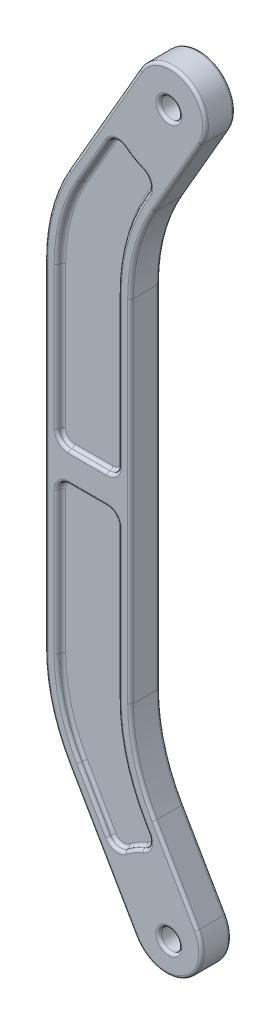
SolidWorks part; units mm, degrees
ref_plane "Front" through (0, 0, 0) normal (0, 0, 1) x (1, 0, 0)
ref_plane "Top" through (0, 0, 0) normal (0, 1, 0) x (1, 0, 0)
ref_plane "Right" through (0, 0, 0) normal (1, 0, 0) x (0, 0, -1)
sketch "Sketch1" plane through (205958.5565, -6567.3917, 0) normal (0, 0, 1) x (1, 0, 0)
  line L0 (-206148.239, 7463.2763) -> (-206157.9214, 7463.2763)
  line L1 (-206148.239, 7132.1417) -> (-206157.9214, 7132.1417)
  line L2 (-206148.239, 7221.6417) -> (-206157.9215, 7221.6417)
  line L3 (-206157.9214, 6891.5071) -> (-206148.239, 6891.5071)
  line L4 (-206158.5565, 7463.2763) -> (-206158.5565, 6891.5071)
  line L5 (-206168.5565, 6891.5071) -> (-206168.5565, 7463.2763)
  line L6 (-206157.9214, 6891.5071) -> (-206157.9214, 7132.1417)
  line L7 (-206168.5565, 6891.5071) -> (-206158.5565, 6891.5071)
  line L8 (-206157.9215, 7221.6417) -> (-206157.9214, 7463.2763)
  line L9 (-206168.5565, 7463.2763) -> (-206158.5565, 7463.2763)
  line L10 (-206033.5565, 6880.3597) -> (-206033.5565, 7474.4236)
  line L11 (-206023.5565, 7474.4236) -> (-206023.5565, 6880.3597)
  line L12 (-206015.0966, 6545.322) -> (-206128.3641, 6741.5071)
  line L13 (-205983.3641, 6730.3598) -> (-205911.1736, 6605.322)
  line L14 (-206102.3834, 6756.5071) -> (-206053.8193, 6672.3917)
  line L15 (-205992.5744, 6725.0422) -> (-205985.0873, 6712.0741)
  line L16 (-206070.5898, 6662.7092) -> (-206119.1539, 6746.8247)
  line L17 (-206110.7686, 6751.6659) -> (-206062.2046, 6667.5505)
  line L18 (-205993.4726, 6707.2329) -> (-206000.9597, 6720.201)
  line L19 (-206009.3449, 6715.3597) -> (-206000.9597, 6720.201)
  line L20 (-205936.0218, 6628.3604) -> (-205992.0244, 6725.3598)
  line L21 (-206119.7039, 6746.5071) -> (-206022.6243, 6578.3604)
  line L22 (-206005.9395, 6529.4614) -> (-205911.1736, 6605.322)
  line L23 (-206001.8578, 6702.3917) -> (-206009.3449, 6715.3597)
  line L24 (-206026.9942, 6654.3193) -> (-206032.9837, 6661.9269)
  line L25 (-206070.5898, 6662.7092) -> (-206062.2046, 6667.5505)
  line L26 (-205985.0873, 6712.0741) -> (-205993.4726, 6707.2329)
  line L27 (-205999.6192, 6670.1243) -> (-206003.2128, 6679.1151)
  line L28 (-206006.8065, 6688.106) -> (-206003.2128, 6679.1151)
  line L29 (-206001.8578, 6702.3917) -> (-205993.4726, 6707.2329)
  line L30 (-206038.9732, 6669.5345) -> (-206032.9837, 6661.9269)
  line L31 (-206053.8193, 6672.3917) -> (-206062.2046, 6667.5505)
  line L32 (-206138.5565, 7132.1417) -> (-206138.5565, 6891.5071)
  line L33 (-206053.5565, 6880.3598) -> (-206053.5565, 7132.1417)
  line L34 (-206034.1916, 7132.1417) -> (-206034.1916, 6880.3598)
  line L35 (-206148.239, 7132.1417) -> (-206148.239, 6891.5071)
  line L36 (-206043.8741, 6880.3598) -> (-206043.8741, 7132.1417)
  line L37 (-206043.8741, 6880.3598) -> (-206034.1916, 6880.3598)
  line L38 (-206053.5565, 6880.3598) -> (-206043.8741, 6880.3598)
  line L39 (-206148.239, 6891.5071) -> (-206138.5565, 6891.5071)
  line L40 (-206033.5565, 6880.3597) -> (-206023.5565, 6880.3597)
  line L41 (-206119.1539, 6746.8247) -> (-206110.7686, 6751.6659)
  line L42 (-206000.9597, 6720.201) -> (-205992.5744, 6725.0422)
  line L43 (-206110.7686, 6751.6659) -> (-206102.3834, 6756.5071)
  line L44 (-205992.0244, 6725.3598) -> (-205983.3641, 6730.3598)
  line L45 (-206128.3641, 6741.5071) -> (-206119.7039, 6746.5071)
  line L46 (-206043.8741, 7132.1417) -> (-206034.1916, 7132.1417)
  line L47 (-206043.8741, 7132.1417) -> (-206053.5565, 7132.1417)
  line L48 (-206148.239, 7132.1417) -> (-206138.5565, 7132.1417)
  line L49 (-206138.5565, 7463.2763) -> (-206138.5565, 7221.6417)
  line L50 (-206053.5565, 7221.6417) -> (-206053.5565, 7474.4236)
  line L51 (-206043.8741, 7221.6417) -> (-206043.8741, 7474.4236)
  line L52 (-206034.1916, 7474.4236) -> (-206034.1916, 7221.6417)
  line L53 (-206148.239, 7463.2763) -> (-206148.239, 7221.6417)
  line L54 (-206128.5565, 7211.6417) -> (-206063.5565, 7211.6417)
  line L55 (-206063.5565, 7142.1417) -> (-206128.5565, 7142.1417)
  line L56 (-206063.5565, 7192.2768) -> (-206128.5565, 7192.2768)
  line L57 (-206128.5565, 7201.9592) -> (-206063.5565, 7201.9592)
  line L58 (-206128.5565, 7161.5066) -> (-206063.5565, 7161.5066)
  line L59 (-206063.5565, 7151.8242) -> (-206128.5565, 7151.8242)
  line L60 (-206063.5565, 7151.8242) -> (-206063.5565, 7161.5066)
  line L61 (-206128.5565, 7151.8242) -> (-206128.5565, 7161.5066)
  line L62 (-206043.8741, 7221.6417) -> (-206034.1916, 7221.6417)
  line L63 (-206063.5565, 7201.9592) -> (-206063.5565, 7192.2768)
  line L64 (-206128.5565, 7201.9592) -> (-206128.5565, 7192.2768)
  line L65 (-206063.5565, 7151.8242) -> (-206063.5565, 7142.1417)
  line L66 (-206128.5565, 7151.8242) -> (-206128.5565, 7142.1417)
  line L67 (-206053.5565, 7221.6417) -> (-206043.8741, 7221.6417)
  line L68 (-206063.5565, 7211.6417) -> (-206063.5565, 7201.9592)
  line L69 (-206128.5565, 7211.6417) -> (-206128.5565, 7201.9592)
  line L70 (-206138.5565, 7221.6417) -> (-206148.239, 7221.6417)
  line L71 (-206034.1916, 7474.4236) -> (-206043.8741, 7474.4236)
  line L72 (-206043.8741, 7474.4236) -> (-206053.5565, 7474.4236)
  line L73 (-206138.5565, 7463.2763) -> (-206148.239, 7463.2763)
  line L74 (-206033.5565, 7474.4236) -> (-206023.5565, 7474.4236)
  line L75 (-206128.3641, 7613.2763) -> (-206008.3812, 7821.0928)
  line L76 (-206008.3812, 7821.0928) -> (-205908.7057, 7753.7358)
  line L77 (-205904.4581, 7761.0928) -> (-205983.3641, 7624.4236)
  line L78 (-205999.6192, 7684.6591) -> (-206003.2128, 7675.6683)
  line L79 (-206026.9942, 7700.4641) -> (-206032.9837, 7692.8565)
  line L80 (-206070.5898, 7692.0741) -> (-206062.2046, 7687.2329)
  line L81 (-206062.2046, 7687.2329) -> (-206053.8193, 7682.3917)
  line L82 (-206003.2128, 7675.6683) -> (-206006.8065, 7666.6774)
  line L83 (-206032.9837, 7692.8565) -> (-206038.9732, 7685.2488)
  line L84 (-205985.0873, 7642.7092) -> (-205992.5744, 7629.7412)
  line L85 (-206000.9597, 7634.5824) -> (-205993.4725, 7647.5505)
  line L86 (-205992.5744, 7629.7412) -> (-206000.9597, 7634.5824)
  line L87 (-205985.0873, 7642.7092) -> (-205993.4725, 7647.5505)
  line L88 (-206110.7687, 7603.1175) -> (-206119.1539, 7607.9587)
  line L89 (-206000.9597, 7634.5824) -> (-206009.3449, 7639.4236)
  line L90 (-206102.3834, 7598.2763) -> (-206110.7687, 7603.1175)
  line L91 (-206128.3641, 7613.2763) -> (-206119.7039, 7608.2763)
  line L92 (-205992.0244, 7629.4236) -> (-205983.3641, 7624.4236)
  line L93 (-206053.8193, 7682.3917) -> (-206102.3834, 7598.2763)
  line L94 (-206009.3449, 7639.4236) -> (-206001.8578, 7652.3917)
  line L95 (-206119.1539, 7607.9587) -> (-206070.5898, 7692.0741)
  line L96 (-206062.2046, 7687.2329) -> (-206110.7687, 7603.1175)
  line L97 (-205993.4725, 7647.5505) -> (-206001.8578, 7652.3917)
  line L98 (-205992.0244, 7629.4236) -> (-205936.0218, 7726.4229)
  line L99 (-206022.6243, 7776.423) -> (-206119.7039, 7608.2763)
  line L100 (-205958.5083, 7787.3905) -> (-205958.5083, 7881.071)
  arc A0 (-206119.1539, 7607.9587) -> (-206157.9214, 7463.2763) centre (-205868.5565, 7463.2763) ccw
  arc A1 (-206110.7687, 7603.1175) -> (-206148.239, 7463.2763) centre (-205868.5565, 7463.2763) ccw
  arc A2 (-206119.7039, 7608.2763) -> (-206158.5565, 7463.2763) centre (-205868.5565, 7463.2763) ccw
  arc A3 (-206128.3641, 7613.2763) -> (-206168.5565, 7463.2763) centre (-205868.5565, 7463.2763) ccw
  arc A4 (-206157.9215, 7221.6417) -> (-206128.5565, 7192.2768) centre (-206128.5565, 7221.6417) ccw
  arc A5 (-206128.5565, 7161.5066) -> (-206157.9214, 7132.1417) centre (-206128.5565, 7132.1417) ccw
  arc A6 (-206148.239, 6891.5071) -> (-206110.7686, 6751.6659) centre (-205868.5565, 6891.5071) ccw
  arc A7 (-206157.9214, 6891.5071) -> (-206119.1539, 6746.8247) centre (-205868.5565, 6891.5071) ccw
  arc A8 (-206158.5565, 6891.5071) -> (-206119.7039, 6746.5071) centre (-205868.5565, 6891.5071) ccw
  arc A9 (-206168.5565, 6891.5071) -> (-206128.3641, 6741.5071) centre (-205868.5565, 6891.5071) ccw
  arc A10 (-206128.5565, 7142.1417) -> (-206138.5565, 7132.1417) centre (-206128.5565, 7132.1417) ccw
  arc A11 (-206053.5565, 7132.1417) -> (-206063.5565, 7142.1417) centre (-206063.5565, 7132.1417) ccw
  arc A12 (-206034.1916, 7132.1417) -> (-206063.5565, 7161.5066) centre (-206063.5565, 7132.1417) ccw
  arc A13 (-206128.5565, 7151.8242) -> (-206148.239, 7132.1417) centre (-206128.5565, 7132.1417) ccw
  arc A14 (-206043.8741, 7132.1417) -> (-206063.5565, 7151.8241) centre (-206063.5565, 7132.1417) ccw
  arc A15 (-206053.5565, 6880.3598) -> (-206009.3449, 6715.3597) centre (-205723.5565, 6880.3597) ccw
  arc A16 (-206015.0966, 6545.322) -> (-205911.1736, 6605.322) centre (-205963.1351, 6575.322) ccw
  arc A17 (-205942.308, 6573.8905) -> (-205947.8321, 6553.5629) centre (-205958.5565, 6567.3917) ccw
  arc A18 (-205942.3082, 6573.8905) -> (-205947.8321, 6553.5631) centre (-205958.5565, 6567.3917) ccw
  arc A19 (-205942.3082, 6573.8905) -> (-205947.8321, 6553.5631) centre (-205958.5565, 6567.3917) ccw
  arc A20 (-205943.3896, 6573.8905) -> (-205947.0556, 6555.5595) centre (-205958.5565, 6567.3917) ccw
  arc A21 (-206053.8193, 6672.3917) -> (-206038.9732, 6669.5345) centre (-206045.1591, 6677.3917) ccw
  arc A22 (-206006.8065, 6688.106) -> (-206001.8578, 6702.3917) centre (-206010.5181, 6697.3917) ccw
  arc A23 (-206006.8065, 6688.106) -> (-206038.9732, 6669.5345) centre (-205958.5565, 6567.3917) ccw
  arc A24 (-205999.6192, 6670.1243) -> (-205985.0873, 6712.0741) centre (-206010.5181, 6697.3917) ccw
  arc A25 (-205999.6192, 6670.1243) -> (-206026.9942, 6654.3193) centre (-205958.5565, 6567.3917) ccw
  arc A26 (-206070.5898, 6662.7092) -> (-206026.9942, 6654.3193) centre (-206045.1591, 6677.3917) ccw
  arc A27 (-206003.2128, 6679.1151) -> (-205993.4726, 6707.2329) centre (-206010.5181, 6697.3917) ccw
  arc A28 (-206003.2128, 6679.1151) -> (-206032.9837, 6661.9269) centre (-205958.5565, 6567.3917) ccw
  arc A29 (-206062.2046, 6667.5505) -> (-206032.9837, 6661.9269) centre (-206045.1591, 6677.3917) ccw
  arc A30 (-206138.5565, 6891.5071) -> (-206102.3834, 6756.5071) centre (-205868.5565, 6891.5071) ccw
  arc A31 (-206034.1916, 6880.3598) -> (-205992.5744, 6725.0422) centre (-205723.5565, 6880.3597) ccw
  arc A32 (-206043.8741, 6880.3598) -> (-206000.9597, 6720.201) centre (-205723.5565, 6880.3597) ccw
  arc A33 (-206033.5565, 6880.3597) -> (-205992.0244, 6725.3598) centre (-205723.5565, 6880.3597) ccw
  arc A34 (-206023.5565, 6880.3597) -> (-205983.3641, 6730.3598) centre (-205723.5565, 6880.3597) ccw
  arc A35 (-206102.3834, 7598.2763) -> (-206138.5565, 7463.2763) centre (-205868.5565, 7463.2763) ccw
  arc A36 (-206009.3449, 7639.4236) -> (-206053.5565, 7474.4236) centre (-205723.5565, 7474.4236) ccw
  arc A37 (-205992.5744, 7629.7412) -> (-206034.1916, 7474.4236) centre (-205723.5565, 7474.4236) ccw
  arc A38 (-206000.9597, 7634.5824) -> (-206043.8741, 7474.4236) centre (-205723.5565, 7474.4236) ccw
  arc A39 (-205983.3641, 7624.4236) -> (-206023.5565, 7474.4236) centre (-205723.5565, 7474.4236) ccw
  arc A40 (-205992.0244, 7629.4236) -> (-206033.5565, 7474.4236) centre (-205723.5565, 7474.4236) ccw
  arc A41 (-206138.5565, 7221.6417) -> (-206128.5565, 7211.6417) centre (-206128.5565, 7221.6417) ccw
  arc A42 (-206063.5565, 7211.6417) -> (-206053.5565, 7221.6417) centre (-206063.5565, 7221.6417) ccw
  arc A43 (-206063.5565, 7192.2768) -> (-206034.1916, 7221.6417) centre (-206063.5565, 7221.6417) ccw
  arc A44 (-206063.5565, 7201.9592) -> (-206043.8741, 7221.6417) centre (-206063.5565, 7221.6417) ccw
  arc A45 (-206148.239, 7221.6417) -> (-206128.5565, 7201.9592) centre (-206128.5565, 7221.6417) ccw
  arc A46 (-205904.4581, 7761.0928) -> (-206008.3812, 7821.0928) centre (-205956.4197, 7791.0928) ccw
  circle A47 centre (-205958.5083, 7787.3905) radius 17.5
  circle A48 centre (-205958.5083, 7787.3905) radius 17.4998
  circle A49 centre (-205958.5083, 7787.3905) radius 17.4998
  circle A50 centre (-205958.5083, 7787.3905) radius 16.5007
  arc A51 (-206001.8578, 7652.3917) -> (-206006.8065, 7666.6774) centre (-206010.5181, 7657.3917) ccw
  arc A52 (-206038.9732, 7685.2488) -> (-206053.8193, 7682.3917) centre (-206045.1591, 7677.3917) ccw
  arc A53 (-206038.9732, 7685.2488) -> (-206006.8065, 7666.6774) centre (-205958.5565, 7787.3917) ccw
  arc A54 (-206026.9942, 7700.4641) -> (-206070.5898, 7692.0741) centre (-206045.1591, 7677.3917) ccw
  arc A55 (-206026.9942, 7700.4641) -> (-205999.6192, 7684.6591) centre (-205958.5565, 7787.3917) ccw
  arc A56 (-206032.9837, 7692.8565) -> (-206003.2128, 7675.6683) centre (-205958.5565, 7787.3917) ccw
  arc A57 (-206032.9837, 7692.8565) -> (-206062.2046, 7687.2329) centre (-206045.1591, 7677.3917) ccw
  arc A58 (-205985.0873, 7642.7092) -> (-205999.6192, 7684.6591) centre (-206010.5181, 7657.3917) ccw
  arc A59 (-205993.4725, 7647.5505) -> (-206003.2128, 7675.6683) centre (-206010.5181, 7657.3917) ccw
sketch "Sketch2" plane through (205958.5083, 0, 8147.7202) normal (0, 1, 0) x (1, 0, 0)
  line L0 (-206153.0161, 8191.7202) -> (-206189.5083, 8191.7202)
  line L1 (-206129.5083, 8116.7202) -> (-206182.5083, 8116.7202)
  line L2 (-206119.7039, 8122.7201) -> (-206158.5565, 8122.7201)
  line L3 (-206168.5565, 8132.7201) -> (-206128.3641, 8132.7201)
  line L4 (-206158.5565, 8172.7201) -> (-206119.7039, 8172.7201)
  line L5 (-206128.3641, 8162.7201) -> (-206168.5565, 8162.7201)
  line L6 (-206189.5083, 8111.7202) -> (-206189.5083, 8086.7202)
  line L7 (-206189.5083, 8196.7202) -> (-206189.5083, 8191.7202)
  line L8 (-206182.5083, 8116.7202) -> (-206189.5083, 8111.7202)
  line L9 (-206168.5565, 8132.7201) -> (-206168.5565, 8162.7201)
  line L10 (-205958.5083, 8027.0014) -> (-205958.5083, 8253.5128)
  line L11 (-206128.5083, 8086.7202) -> (-206128.5083, 8116.7202)
  line L12 (-206129.5083, 8086.7202) -> (-206129.5083, 8116.7202)
  line L13 (-205975.8565, 8112.2199) -> (-205975.8565, 8097.797)
  line L14 (-205900.0756, 8127.7202) -> (-205900.0767, 8127.6564)
  line L15 (-205900.0767, 8127.6564) -> (-205900.0778, 8127.5926)
  line L16 (-205900.0778, 8127.5926) -> (-205900.0789, 8127.5288)
  line L17 (-205900.0789, 8127.5288) -> (-205900.0801, 8127.465)
  line L18 (-205900.0801, 8127.465) -> (-205900.0813, 8127.4012)
  line L19 (-205900.0813, 8127.4012) -> (-205900.0825, 8127.3374)
  line L20 (-205900.0825, 8127.3374) -> (-205900.0837, 8127.2736)
  line L21 (-205900.0837, 8127.2736) -> (-205900.085, 8127.2098)
  line L22 (-205900.085, 8127.2098) -> (-205900.0864, 8127.146)
  line L23 (-205900.0864, 8127.146) -> (-205900.0877, 8127.0823)
  line L24 (-205900.0877, 8127.0823) -> (-205900.0891, 8127.022)
  line L25 (-205900.0891, 8127.022) -> (-205900.0904, 8126.9617)
  line L26 (-205900.0904, 8126.9617) -> (-205900.0919, 8126.9014)
  line L27 (-205900.0919, 8126.9014) -> (-205900.0934, 8126.8411)
  line L28 (-205900.0934, 8126.8411) -> (-205900.0949, 8126.7808)
  line L29 (-205900.0949, 8126.7808) -> (-205900.0965, 8126.7205)
  line L30 (-205900.0965, 8126.7205) -> (-205900.0981, 8126.6602)
  line L31 (-205900.0981, 8126.6602) -> (-205900.0999, 8126.5999)
  line L32 (-205900.0999, 8126.5999) -> (-205900.1016, 8126.5396)
  line L33 (-205900.1016, 8126.5396) -> (-205900.1035, 8126.4794)
  line L34 (-205900.1035, 8126.4794) -> (-205900.1054, 8126.4211)
  line L35 (-205900.1054, 8126.4211) -> (-205900.1073, 8126.3629)
  line L36 (-205900.1073, 8126.3629) -> (-205900.1093, 8126.3046)
  line L37 (-205900.1093, 8126.3046) -> (-205900.1114, 8126.2464)
  line L38 (-205900.1114, 8126.2464) -> (-205900.1136, 8126.1882)
  line L39 (-205900.1136, 8126.1882) -> (-205900.1158, 8126.1299)
  line L40 (-205900.1158, 8126.1299) -> (-205900.1181, 8126.0717)
  line L41 (-205900.1181, 8126.0717) -> (-205900.1206, 8126.0135)
  line L42 (-205900.1206, 8126.0135) -> (-205900.1231, 8125.9553)
  line L43 (-205900.1231, 8125.9553) -> (-205900.1257, 8125.897)
  line L44 (-205900.1257, 8125.897) -> (-205900.1284, 8125.8394)
  line L45 (-205900.1284, 8125.8394) -> (-205900.1311, 8125.7818)
  line L46 (-205900.1311, 8125.7818) -> (-205900.134, 8125.7242)
  line L47 (-205900.134, 8125.7242) -> (-205900.137, 8125.6665)
  line L48 (-205900.137, 8125.6665) -> (-205900.14, 8125.6089)
  line L49 (-205900.14, 8125.6089) -> (-205900.1432, 8125.5513)
  line L50 (-205900.1432, 8125.5513) -> (-205900.1465, 8125.4937)
  line L51 (-205900.1465, 8125.4937) -> (-205900.1499, 8125.4361)
  line L52 (-205900.1499, 8125.4361) -> (-205900.1534, 8125.3785)
  line L53 (-205900.1534, 8125.3785) -> (-205900.157, 8125.3209)
  line L54 (-205900.157, 8125.3209) -> (-205900.1647, 8125.204)
  line L55 (-205900.1647, 8125.204) -> (-205900.1728, 8125.087)
  line L56 (-205900.1728, 8125.087) -> (-205900.1814, 8124.9701)
  line L57 (-205900.1814, 8124.9701) -> (-205900.1905, 8124.8532)
  line L58 (-205900.1905, 8124.8532) -> (-205900.1999, 8124.7364)
  line L59 (-205900.1999, 8124.7364) -> (-205900.2099, 8124.6196)
  line L60 (-205900.2099, 8124.6196) -> (-205900.2202, 8124.5028)
  line L61 (-205900.2202, 8124.5028) -> (-205900.231, 8124.3861)
  line L62 (-205900.231, 8124.3861) -> (-205900.2422, 8124.2694)
  line L63 (-205900.2422, 8124.2694) -> (-205900.2538, 8124.1527)
  line L64 (-205900.2538, 8124.1527) -> (-205900.2661, 8124.0338)
  line L65 (-205900.2661, 8124.0338) -> (-205900.2788, 8123.9149)
  line L66 (-205900.2788, 8123.9149) -> (-205900.2919, 8123.796)
  line L67 (-205900.2919, 8123.796) -> (-205900.3055, 8123.6772)
  line L68 (-205900.3055, 8123.6772) -> (-205900.3195, 8123.5584)
  line L69 (-205900.3195, 8123.5584) -> (-205900.3339, 8123.4397)
  line L70 (-205900.3339, 8123.4397) -> (-205900.3487, 8123.3211)
  line L71 (-205900.3487, 8123.3211) -> (-205900.3639, 8123.2024)
  line L72 (-205900.3639, 8123.2024) -> (-205900.3795, 8123.0839)
  line L73 (-205900.3795, 8123.0839) -> (-205900.3956, 8122.9654)
  line L74 (-205900.3956, 8122.9654) -> (-205900.4122, 8122.8458)
  line L75 (-205900.4122, 8122.8458) -> (-205900.4292, 8122.7263)
  line L76 (-205900.4292, 8122.7263) -> (-205900.4466, 8122.6069)
  line L77 (-205900.4466, 8122.6069) -> (-205900.4644, 8122.4875)
  line L78 (-205900.4644, 8122.4875) -> (-205900.4826, 8122.3682)
  line L79 (-205900.4826, 8122.3682) -> (-205900.5013, 8122.2489)
  line L80 (-205900.5013, 8122.2489) -> (-205900.5203, 8122.1297)
  line L81 (-205900.5203, 8122.1297) -> (-205900.5398, 8122.0106)
  line L82 (-205900.5398, 8122.0106) -> (-205900.5596, 8121.8915)
  line L83 (-205900.5596, 8121.8915) -> (-205900.5798, 8121.7725)
  line L84 (-205900.5798, 8121.7725) -> (-205900.6005, 8121.6537)
  line L85 (-205900.6005, 8121.6537) -> (-205900.6215, 8121.535)
  line L86 (-205900.6215, 8121.535) -> (-205900.6429, 8121.4163)
  line L87 (-205900.6429, 8121.4163) -> (-205900.6648, 8121.2977)
  line L88 (-205900.6648, 8121.2977) -> (-205900.687, 8121.1791)
  line L89 (-205900.687, 8121.1791) -> (-205900.7096, 8121.0607)
  line L90 (-205900.7096, 8121.0607) -> (-205900.7327, 8120.9423)
  line L91 (-205900.7327, 8120.9423) -> (-205900.7561, 8120.824)
  line L92 (-205900.7561, 8120.824) -> (-205900.7799, 8120.7058)
  line L93 (-205900.7799, 8120.7058) -> (-205900.8042, 8120.5877)
  line L94 (-205900.8042, 8120.5877) -> (-205900.8286, 8120.4707)
  line L95 (-205900.8286, 8120.4707) -> (-205900.8535, 8120.3538)
  line L96 (-205900.8535, 8120.3538) -> (-205900.8787, 8120.2369)
  line L97 (-205900.8787, 8120.2369) -> (-205900.9043, 8120.1202)
  line L98 (-205900.9043, 8120.1202) -> (-205900.9304, 8120.0035)
  line L99 (-205900.9304, 8120.0035) -> (-205900.9568, 8119.887)
  line L100 (-205900.9568, 8119.887) -> (-205900.9837, 8119.7705)
  line L101 (-205900.9837, 8119.7705) -> (-205901.0109, 8119.6541)
  line L102 (-205901.0109, 8119.6541) -> (-205901.0386, 8119.5379)
  line L103 (-205901.0386, 8119.5379) -> (-205901.0666, 8119.4217)
  line L104 (-205901.0666, 8119.4217) -> (-205901.0949, 8119.3067)
  line L105 (-205901.0949, 8119.3067) -> (-205901.1235, 8119.1917)
  line L106 (-205901.1235, 8119.1917) -> (-205901.1525, 8119.0769)
  line L107 (-205901.1525, 8119.0769) -> (-205901.1819, 8118.9622)
  line L108 (-205901.1819, 8118.9622) -> (-205901.2117, 8118.8476)
  line L109 (-205901.2117, 8118.8476) -> (-205901.2419, 8118.733)
  line L110 (-205901.2419, 8118.733) -> (-205901.2725, 8118.6186)
  line L111 (-205901.2725, 8118.6186) -> (-205901.3035, 8118.5043)
  line L112 (-205901.3035, 8118.5043) -> (-205901.3349, 8118.3901)
  line L113 (-205901.3349, 8118.3901) -> (-205901.3667, 8118.2761)
  line L114 (-205901.3667, 8118.2761) -> (-205901.3987, 8118.1629)
  line L115 (-205901.3987, 8118.1629) -> (-205901.4311, 8118.0498)
  line L116 (-205901.4311, 8118.0498) -> (-205901.4639, 8117.9369)
  line L117 (-205901.4639, 8117.9369) -> (-205901.4971, 8117.824)
  line L118 (-205901.4971, 8117.824) -> (-205901.5307, 8117.7113)
  line L119 (-205901.5307, 8117.7113) -> (-205901.5646, 8117.5987)
  line L120 (-205901.5646, 8117.5987) -> (-205901.599, 8117.4862)
  line L121 (-205901.599, 8117.4862) -> (-205901.6338, 8117.3739)
  line L122 (-205901.6338, 8117.3739) -> (-205901.6689, 8117.2616)
  line L123 (-205901.6689, 8117.2616) -> (-205901.7045, 8117.1495)
  line L124 (-205901.7045, 8117.1495) -> (-205901.7402, 8117.0381)
  line L125 (-205901.7402, 8117.0381) -> (-205901.7764, 8116.9267)
  line L126 (-205901.7764, 8116.9267) -> (-205901.813, 8116.8155)
  line L127 (-205901.813, 8116.8155) -> (-205901.8499, 8116.7045)
  line L128 (-205901.8499, 8116.7045) -> (-205901.8873, 8116.5935)
  line L129 (-205901.8873, 8116.5935) -> (-205901.925, 8116.4827)
  line L130 (-205901.925, 8116.4827) -> (-205901.9631, 8116.372)
  line L131 (-205901.9631, 8116.372) -> (-205902.0016, 8116.2615)
  line L132 (-205902.0016, 8116.2615) -> (-205902.0405, 8116.1511)
  line L133 (-205902.0405, 8116.1511) -> (-205902.0798, 8116.0408)
  line L134 (-205902.0798, 8116.0408) -> (-205902.1193, 8115.9311)
  line L135 (-205902.1193, 8115.9311) -> (-205902.1593, 8115.8214)
  line L136 (-205902.1593, 8115.8214) -> (-205902.1996, 8115.7119)
  line L137 (-205902.1996, 8115.7119) -> (-205902.2403, 8115.6026)
  line L138 (-205902.2403, 8115.6026) -> (-205902.2814, 8115.4934)
  line L139 (-205902.2814, 8115.4934) -> (-205902.3228, 8115.3843)
  line L140 (-205902.3228, 8115.3843) -> (-205902.3647, 8115.2754)
  line L141 (-205902.3647, 8115.2754) -> (-205902.4069, 8115.1666)
  line L142 (-205902.4069, 8115.1666) -> (-205902.4495, 8115.058)
  line L143 (-205902.4495, 8115.058) -> (-205902.4925, 8114.9496)
  line L144 (-205902.4925, 8114.9496) -> (-205902.5357, 8114.8416)
  line L145 (-205902.5357, 8114.8416) -> (-205902.5793, 8114.7339)
  line L146 (-205902.5793, 8114.7339) -> (-205902.6233, 8114.6263)
  line L147 (-205902.6233, 8114.6263) -> (-205902.6677, 8114.5188)
  line L148 (-205902.6677, 8114.5188) -> (-205902.7124, 8114.4115)
  line L149 (-205902.7124, 8114.4115) -> (-205902.7575, 8114.3044)
  line L150 (-205902.7575, 8114.3044) -> (-205902.803, 8114.1974)
  line L151 (-205902.803, 8114.1974) -> (-205902.8489, 8114.0906)
  line L152 (-205902.8489, 8114.0906) -> (-205902.8951, 8113.9839)
  line L153 (-205902.8951, 8113.9839) -> (-205902.9418, 8113.8774)
  line L154 (-205902.9418, 8113.8774) -> (-205902.9886, 8113.7716)
  line L155 (-205902.9886, 8113.7716) -> (-205903.0357, 8113.666)
  line L156 (-205903.0357, 8113.666) -> (-205903.0833, 8113.5605)
  line L157 (-205903.0833, 8113.5605) -> (-205903.1312, 8113.4552)
  line L158 (-205903.1312, 8113.4552) -> (-205903.1795, 8113.3501)
  line L159 (-205903.1795, 8113.3501) -> (-205903.2281, 8113.2451)
  line L160 (-205903.2281, 8113.2451) -> (-205903.2772, 8113.1403)
  line L161 (-205903.2772, 8113.1403) -> (-205903.3266, 8113.0357)
  line L162 (-205903.3266, 8113.0357) -> (-205903.3764, 8112.9313)
  line L163 (-205903.3764, 8112.9313) -> (-205903.4266, 8112.827)
  line L164 (-205903.4266, 8112.827) -> (-205903.4768, 8112.7236)
  line L165 (-205903.4768, 8112.7236) -> (-205903.5275, 8112.6203)
  line L166 (-205903.5275, 8112.6203) -> (-205903.5785, 8112.5172)
  line L167 (-205903.5785, 8112.5172) -> (-205903.6298, 8112.4143)
  line L168 (-205903.6298, 8112.4143) -> (-205903.6816, 8112.3116)
  line L169 (-205903.6816, 8112.3116) -> (-205903.7337, 8112.209)
  line L170 (-205903.7337, 8112.209) -> (-205903.7862, 8112.1067)
  line L171 (-205903.7862, 8112.1067) -> (-205903.8391, 8112.0046)
  line L172 (-205903.8391, 8112.0046) -> (-205903.8923, 8111.9026)
  line L173 (-205903.8923, 8111.9026) -> (-205903.9459, 8111.8009)
  line L174 (-205903.9459, 8111.8009) -> (-205903.9996, 8111.6999)
  line L175 (-205903.9996, 8111.6999) -> (-205904.0536, 8111.5992)
  line L176 (-205904.0536, 8111.5992) -> (-205904.108, 8111.4987)
  line L177 (-205904.108, 8111.4987) -> (-205904.1628, 8111.3984)
  line L178 (-205904.1628, 8111.3984) -> (-205904.2179, 8111.2982)
  line L179 (-205904.2179, 8111.2982) -> (-205904.2734, 8111.1983)
  line L180 (-205904.2734, 8111.1983) -> (-205904.3293, 8111.0986)
  line L181 (-205904.3293, 8111.0986) -> (-205904.3855, 8110.9991)
  line L182 (-205904.3855, 8110.9991) -> (-205904.4421, 8110.8998)
  line L183 (-205904.4421, 8110.8998) -> (-205904.4991, 8110.8007)
  line L184 (-205904.4991, 8110.8007) -> (-205904.5561, 8110.7025)
  line L185 (-205904.5561, 8110.7025) -> (-205904.6134, 8110.6046)
  line L186 (-205904.6134, 8110.6046) -> (-205904.671, 8110.5068)
  line L187 (-205904.671, 8110.5068) -> (-205904.729, 8110.4093)
  line L188 (-205904.729, 8110.4093) -> (-205904.7874, 8110.312)
  line L189 (-205904.7874, 8110.312) -> (-205904.8462, 8110.2148)
  line L190 (-205904.8462, 8110.2148) -> (-205904.9053, 8110.118)
  line L191 (-205904.9053, 8110.118) -> (-205904.9648, 8110.0213)
  line L192 (-205904.9648, 8110.0213) -> (-205905.0246, 8109.9249)
  line L193 (-205905.0246, 8109.9249) -> (-205905.0848, 8109.8287)
  line L194 (-205905.0848, 8109.8287) -> (-205905.1449, 8109.7334)
  line L195 (-205905.1449, 8109.7334) -> (-205905.2054, 8109.6383)
  line L196 (-205905.2054, 8109.6383) -> (-205905.2662, 8109.5434)
  line L197 (-205905.2662, 8109.5434) -> (-205905.3274, 8109.4488)
  line L198 (-205905.3274, 8109.4488) -> (-205905.3889, 8109.3544)
  line L199 (-205905.3889, 8109.3544) -> (-205905.4508, 8109.2603)
  line L200 (-205905.4508, 8109.2603) -> (-205905.5131, 8109.1664)
  line L201 (-205905.5131, 8109.1664) -> (-205905.5757, 8109.0727)
  line L202 (-205905.5757, 8109.0727) -> (-205905.6386, 8108.9792)
  line L203 (-205905.6386, 8108.9792) -> (-205905.7019, 8108.886)
  line L204 (-205905.7019, 8108.886) -> (-205905.7651, 8108.7937)
  line L205 (-205905.7651, 8108.7937) -> (-205905.8287, 8108.7017)
  line L206 (-205905.8287, 8108.7017) -> (-205905.8925, 8108.6099)
  line L207 (-205905.8925, 8108.6099) -> (-205905.9568, 8108.5183)
  line L208 (-205905.9568, 8108.5183) -> (-205906.0214, 8108.427)
  line L209 (-205906.0214, 8108.427) -> (-205906.0863, 8108.3359)
  line L210 (-205906.0863, 8108.3359) -> (-205906.1516, 8108.245)
  line L211 (-205906.1516, 8108.245) -> (-205906.2172, 8108.1545)
  line L212 (-205906.2172, 8108.1545) -> (-205906.2831, 8108.0641)
  line L213 (-205906.2831, 8108.0641) -> (-205906.3495, 8107.9741)
  line L214 (-205906.3495, 8107.9741) -> (-205906.4157, 8107.8847)
  line L215 (-205906.4157, 8107.8847) -> (-205906.4824, 8107.7957)
  line L216 (-205906.4824, 8107.7957) -> (-205906.5493, 8107.7069)
  line L217 (-205906.5493, 8107.7069) -> (-205906.6166, 8107.6183)
  line L218 (-205906.6166, 8107.6183) -> (-205906.6843, 8107.53)
  line L219 (-205906.6843, 8107.53) -> (-205906.7522, 8107.442)
  line L220 (-205906.7522, 8107.442) -> (-205906.8206, 8107.3542)
  line L221 (-205906.8206, 8107.3542) -> (-205906.8892, 8107.2667)
  line L222 (-205906.8892, 8107.2667) -> (-205906.9582, 8107.1794)
  line L223 (-205906.9582, 8107.1794) -> (-205907.0275, 8107.0925)
  line L224 (-205907.0275, 8107.0925) -> (-205907.0967, 8107.0064)
  line L225 (-205907.0967, 8107.0064) -> (-205907.1661, 8106.9207)
  line L226 (-205907.1661, 8106.9207) -> (-205907.2359, 8106.8352)
  line L227 (-205907.2359, 8106.8352) -> (-205907.3061, 8106.7499)
  line L228 (-205907.3061, 8106.7499) -> (-205907.3765, 8106.665)
  line L229 (-205907.3765, 8106.665) -> (-205907.4473, 8106.5803)
  line L230 (-205907.4473, 8106.5803) -> (-205907.5184, 8106.4959)
  line L231 (-205907.5184, 8106.4959) -> (-205907.5899, 8106.4117)
  line L232 (-205907.5899, 8106.4117) -> (-205907.6616, 8106.3279)
  line L233 (-205907.6616, 8106.3279) -> (-205907.7337, 8106.2443)
  line L234 (-205907.7337, 8106.2443) -> (-205907.8056, 8106.1617)
  line L235 (-205907.8056, 8106.1617) -> (-205907.8777, 8106.0793)
  line L236 (-205907.8777, 8106.0793) -> (-205907.9502, 8105.9972)
  line L237 (-205907.9502, 8105.9972) -> (-205908.023, 8105.9155)
  line L238 (-205908.023, 8105.9155) -> (-205908.0962, 8105.8339)
  line L239 (-205908.0962, 8105.8339) -> (-205908.1696, 8105.7527)
  line L240 (-205908.1696, 8105.7527) -> (-205908.2434, 8105.6718)
  line L241 (-205908.2434, 8105.6718) -> (-205908.3175, 8105.5912)
  line L242 (-205908.3175, 8105.5912) -> (-205908.3919, 8105.5108)
  line L243 (-205908.3919, 8105.5108) -> (-205908.4666, 8105.4308)
  line L244 (-205908.4666, 8105.4308) -> (-205908.541, 8105.3517)
  line L245 (-205908.541, 8105.3517) -> (-205908.6158, 8105.2729)
  line L246 (-205908.6158, 8105.2729) -> (-205908.6908, 8105.1944)
  line L247 (-205908.6908, 8105.1944) -> (-205908.7662, 8105.1162)
  line L248 (-205908.7662, 8105.1162) -> (-205908.8418, 8105.0383)
  line L249 (-205908.8418, 8105.0383) -> (-205908.9178, 8104.9607)
  line L250 (-205908.9178, 8104.9607) -> (-205908.9941, 8104.8834)
  line L251 (-205908.9941, 8104.8834) -> (-205909.0707, 8104.8064)
  line L252 (-205909.0707, 8104.8064) -> (-205909.1476, 8104.7297)
  line L253 (-205909.1476, 8104.7297) -> (-205909.2248, 8104.6533)
  line L254 (-205909.2248, 8104.6533) -> (-205909.302, 8104.5776)
  line L255 (-205909.302, 8104.5776) -> (-205909.3794, 8104.5022)
  line L256 (-205909.3794, 8104.5022) -> (-205909.4572, 8104.4272)
  line L257 (-205909.4572, 8104.4272) -> (-205909.5353, 8104.3524)
  line L258 (-205909.5353, 8104.3524) -> (-205909.6137, 8104.2779)
  line L259 (-205909.6137, 8104.2779) -> (-205909.6923, 8104.2038)
  line L260 (-205909.6923, 8104.2038) -> (-205909.7713, 8104.13)
  line L261 (-205909.7713, 8104.13) -> (-205909.8506, 8104.0565)
  line L262 (-205909.8506, 8104.0565) -> (-205909.9301, 8103.9833)
  line L263 (-205909.9301, 8103.9833) -> (-205910.01, 8103.9105)
  line L264 (-205910.01, 8103.9105) -> (-205910.0895, 8103.8386)
  line L265 (-205910.0895, 8103.8386) -> (-205910.1693, 8103.767)
  line L266 (-205910.1693, 8103.767) -> (-205910.2494, 8103.6957)
  line L267 (-205910.2494, 8103.6957) -> (-205910.3298, 8103.6247)
  line L268 (-205910.3298, 8103.6247) -> (-205910.4104, 8103.5541)
  line L269 (-205910.4104, 8103.5541) -> (-205910.4914, 8103.4839)
  line L270 (-205910.4914, 8103.4839) -> (-205910.5726, 8103.4139)
  line L271 (-205910.5726, 8103.4139) -> (-205910.6542, 8103.3443)
  line L272 (-205910.6542, 8103.3443) -> (-205910.736, 8103.275)
  line L273 (-205910.736, 8103.275) -> (-205910.8181, 8103.2061)
  line L274 (-205910.8181, 8103.2061) -> (-205910.8998, 8103.138)
  line L275 (-205910.8998, 8103.138) -> (-205910.9818, 8103.0703)
  line L276 (-205910.9818, 8103.0703) -> (-205911.0641, 8103.003)
  line L277 (-205911.0641, 8103.003) -> (-205911.1467, 8102.9359)
  line L278 (-205911.1467, 8102.9359) -> (-205911.2295, 8102.8693)
  line L279 (-205911.2295, 8102.8693) -> (-205911.3127, 8102.8029)
  line L280 (-205911.3127, 8102.8029) -> (-205911.3961, 8102.7369)
  line L281 (-205911.3961, 8102.7369) -> (-205911.4797, 8102.6713)
  line L282 (-205911.4797, 8102.6713) -> (-205911.5637, 8102.606)
  line L283 (-205911.5637, 8102.606) -> (-205911.6479, 8102.5411)
  line L284 (-205911.6479, 8102.5411) -> (-205911.7317, 8102.477)
  line L285 (-205911.7317, 8102.477) -> (-205911.8158, 8102.4133)
  line L286 (-205911.8158, 8102.4133) -> (-205911.9002, 8102.3499)
  line L287 (-205911.9002, 8102.3499) -> (-205911.9848, 8102.2869)
  line L288 (-205911.9848, 8102.2869) -> (-205912.0697, 8102.2242)
  line L289 (-205912.0697, 8102.2242) -> (-205912.1549, 8102.1619)
  line L290 (-205912.1549, 8102.1619) -> (-205912.2403, 8102.0999)
  line L291 (-205912.2403, 8102.0999) -> (-205912.326, 8102.0383)
  line L292 (-205912.326, 8102.0383) -> (-205912.412, 8101.9771)
  line L293 (-205912.412, 8101.9771) -> (-205912.4982, 8101.9163)
  line L294 (-205912.4982, 8101.9163) -> (-205912.5845, 8101.8559)
  line L295 (-205912.5845, 8101.8559) -> (-205912.6711, 8101.7959)
  line L296 (-205912.6711, 8101.7959) -> (-205912.7579, 8101.7362)
  line L297 (-205912.7579, 8101.7362) -> (-205912.845, 8101.677)
  line L298 (-205912.845, 8101.677) -> (-205912.9323, 8101.6181)
  line L299 (-205912.9323, 8101.6181) -> (-205913.0199, 8101.5595)
  line L300 (-205913.0199, 8101.5595) -> (-205913.1078, 8101.5014)
  line L301 (-205913.1078, 8101.5014) -> (-205913.1959, 8101.4436)
  line L302 (-205913.1959, 8101.4436) -> (-205913.2842, 8101.3862)
  line L303 (-205913.2842, 8101.3862) -> (-205913.3728, 8101.3292)
  line L304 (-205913.3728, 8101.3292) -> (-205913.4609, 8101.273)
  line L305 (-205913.4609, 8101.273) -> (-205913.5493, 8101.2172)
  line L306 (-205913.5493, 8101.2172) -> (-205913.6379, 8101.1618)
  line L307 (-205913.6379, 8101.1618) -> (-205913.7267, 8101.1068)
  line L308 (-205913.7267, 8101.1068) -> (-205913.8158, 8101.0521)
  line L309 (-205913.8158, 8101.0521) -> (-205913.9051, 8100.9978)
  line L310 (-205913.9051, 8100.9978) -> (-205913.9946, 8100.9439)
  line L311 (-205913.9946, 8100.9439) -> (-205914.0844, 8100.8904)
  line L312 (-205914.0844, 8100.8904) -> (-205914.1744, 8100.8373)
  line L313 (-205914.1744, 8100.8373) -> (-205914.2646, 8100.7845)
  line L314 (-205914.2646, 8100.7845) -> (-205914.3543, 8100.7326)
  line L315 (-205914.3543, 8100.7326) -> (-205914.4443, 8100.6811)
  line L316 (-205914.4443, 8100.6811) -> (-205914.5344, 8100.63)
  line L317 (-205914.5344, 8100.63) -> (-205914.6248, 8100.5792)
  line L318 (-205914.6248, 8100.5792) -> (-205914.7154, 8100.5289)
  line L319 (-205914.7154, 8100.5289) -> (-205914.8062, 8100.4789)
  line L320 (-205914.8062, 8100.4789) -> (-205914.8972, 8100.4293)
  line L321 (-205914.8972, 8100.4293) -> (-205914.9885, 8100.3802)
  line L322 (-205914.9885, 8100.3802) -> (-205915.0799, 8100.3314)
  line L323 (-205915.0799, 8100.3314) -> (-205915.1716, 8100.283)
  line L324 (-205915.1716, 8100.283) -> (-205915.2626, 8100.2354)
  line L325 (-205915.2626, 8100.2354) -> (-205915.3539, 8100.1883)
  line L326 (-205915.3539, 8100.1883) -> (-205915.4454, 8100.1415)
  line L327 (-205915.4454, 8100.1415) -> (-205915.5371, 8100.0951)
  line L328 (-205915.5371, 8100.0951) -> (-205915.6289, 8100.0492)
  line L329 (-205915.6289, 8100.0492) -> (-205915.721, 8100.0036)
  line L330 (-205915.721, 8100.0036) -> (-205915.8133, 8099.9584)
  line L331 (-205915.8133, 8099.9584) -> (-205915.9058, 8099.9137)
  line L332 (-205915.9058, 8099.9137) -> (-205915.9985, 8099.8693)
  line L333 (-205915.9985, 8099.8693) -> (-205916.0913, 8099.8254)
  line L334 (-205916.0913, 8099.8254) -> (-205916.1843, 8099.7818)
  line L335 (-205916.1843, 8099.7818) -> (-205916.2775, 8099.7387)
  line L336 (-205916.2775, 8099.7387) -> (-205916.3709, 8099.696)
  line L337 (-205916.3709, 8099.696) -> (-205916.4645, 8099.6538)
  line L338 (-205916.4645, 8099.6538) -> (-205916.5583, 8099.6119)
  line L339 (-205916.5583, 8099.6119) -> (-205916.6523, 8099.5705)
  line L340 (-205916.6523, 8099.5705) -> (-205916.7465, 8099.5295)
  line L341 (-205916.7465, 8099.5295) -> (-205916.8408, 8099.4889)
  line L342 (-205916.8408, 8099.4889) -> (-205916.9353, 8099.4487)
  line L343 (-205916.9353, 8099.4487) -> (-205917.03, 8099.409)
  line L344 (-205917.03, 8099.409) -> (-205917.1243, 8099.3699)
  line L345 (-205917.1243, 8099.3699) -> (-205917.2188, 8099.3313)
  line L346 (-205917.2188, 8099.3313) -> (-205917.3135, 8099.2931)
  line L347 (-205917.3135, 8099.2931) -> (-205917.4083, 8099.2553)
  line L348 (-205917.4083, 8099.2553) -> (-205917.5033, 8099.218)
  line L349 (-205917.5033, 8099.218) -> (-205917.5985, 8099.1811)
  line L350 (-205917.5985, 8099.1811) -> (-205917.6938, 8099.1446)
  line L351 (-205917.6938, 8099.1446) -> (-205917.7894, 8099.1085)
  line L352 (-205917.7894, 8099.1085) -> (-205917.885, 8099.073)
  line L353 (-205917.885, 8099.073) -> (-205917.9809, 8099.0378)
  line L354 (-205917.9809, 8099.0378) -> (-205918.0766, 8099.0032)
  line L355 (-205918.0766, 8099.0032) -> (-205918.1725, 8098.969)
  line L356 (-205918.1725, 8098.969) -> (-205918.2686, 8098.9353)
  line L357 (-205918.2686, 8098.9353) -> (-205918.3648, 8098.902)
  line L358 (-205918.3648, 8098.902) -> (-205918.4612, 8098.8692)
  line L359 (-205918.4612, 8098.8692) -> (-205918.5577, 8098.8368)
  line L360 (-205918.5577, 8098.8368) -> (-205918.6544, 8098.8048)
  line L361 (-205918.6544, 8098.8048) -> (-205918.7512, 8098.7733)
  line L362 (-205918.7512, 8098.7733) -> (-205918.8481, 8098.7423)
  line L363 (-205918.8481, 8098.7423) -> (-205918.9452, 8098.7117)
  line L364 (-205918.9452, 8098.7117) -> (-205919.0426, 8098.6815)
  line L365 (-205919.0426, 8098.6815) -> (-205919.14, 8098.6518)
  line L366 (-205919.14, 8098.6518) -> (-205919.2376, 8098.6225)
  line L367 (-205919.2376, 8098.6225) -> (-205919.3354, 8098.5937)
  line L368 (-205919.3354, 8098.5937) -> (-205919.4333, 8098.5653)
  line L369 (-205919.4333, 8098.5653) -> (-205919.5313, 8098.5374)
  line L370 (-205919.5313, 8098.5374) -> (-205919.6294, 8098.5099)
  line L371 (-205919.6294, 8098.5099) -> (-205919.7277, 8098.4829)
  line L372 (-205919.7277, 8098.4829) -> (-205919.826, 8098.4564)
  line L373 (-205919.826, 8098.4564) -> (-205919.9245, 8098.4303)
  line L374 (-205919.9245, 8098.4303) -> (-205920.0243, 8098.4044)
  line L375 (-205920.0243, 8098.4044) -> (-205920.1242, 8098.3789)
  line L376 (-205920.1242, 8098.3789) -> (-205920.2242, 8098.3539)
  line L377 (-205920.2242, 8098.3539) -> (-205920.3243, 8098.3294)
  line L378 (-205920.3243, 8098.3294) -> (-205920.4246, 8098.3053)
  line L379 (-205920.4246, 8098.3053) -> (-205920.5249, 8098.2817)
  line L380 (-205920.5249, 8098.2817) -> (-205920.6254, 8098.2586)
  line L381 (-205920.6254, 8098.2586) -> (-205920.7259, 8098.2359)
  line L382 (-205920.7259, 8098.2359) -> (-205920.8266, 8098.2137)
  line L383 (-205920.8266, 8098.2137) -> (-205920.9274, 8098.192)
  line L384 (-205920.9274, 8098.192) -> (-205921.0277, 8098.1708)
  line L385 (-205921.0277, 8098.1708) -> (-205921.1281, 8098.1501)
  line L386 (-205921.1281, 8098.1501) -> (-205921.2286, 8098.1299)
  line L387 (-205921.2286, 8098.1299) -> (-205921.3292, 8098.1101)
  line L388 (-205921.3292, 8098.1101) -> (-205921.43, 8098.0908)
  line L389 (-205921.43, 8098.0908) -> (-205921.5307, 8098.0719)
  line L390 (-205921.5307, 8098.0719) -> (-205921.6316, 8098.0535)
  line L391 (-205921.6316, 8098.0535) -> (-205921.7326, 8098.0356)
  line L392 (-205921.7326, 8098.0356) -> (-205921.8336, 8098.0182)
  line L393 (-205921.8336, 8098.0182) -> (-205921.9347, 8098.0012)
  line L394 (-205921.9347, 8098.0012) -> (-205922.0344, 8097.985)
  line L395 (-205922.0344, 8097.985) -> (-205922.1342, 8097.9692)
  line L396 (-205922.1342, 8097.9692) -> (-205922.234, 8097.9539)
  line L397 (-205922.234, 8097.9539) -> (-205922.3339, 8097.9391)
  line L398 (-205922.3339, 8097.9391) -> (-205922.4338, 8097.9247)
  line L399 (-205922.4338, 8097.9247) -> (-205922.5339, 8097.9109)
  line L400 (-205922.5339, 8097.9109) -> (-205922.634, 8097.8975)
  line L401 (-205922.634, 8097.8975) -> (-205922.7341, 8097.8846)
  line L402 (-205922.7341, 8097.8846) -> (-205922.8344, 8097.8722)
  line L403 (-205922.8344, 8097.8722) -> (-205922.9346, 8097.8603)
  line L404 (-205922.9346, 8097.8603) -> (-205923.0324, 8097.8491)
  line L405 (-205923.0324, 8097.8491) -> (-205923.1303, 8097.8385)
  line L406 (-205923.1303, 8097.8385) -> (-205923.2282, 8097.8283)
  line L407 (-205923.2282, 8097.8283) -> (-205923.3262, 8097.8186)
  line L408 (-205923.3262, 8097.8186) -> (-205923.4242, 8097.8094)
  line L409 (-205923.4242, 8097.8094) -> (-205923.5223, 8097.8007)
  line L410 (-205923.5223, 8097.8007) -> (-205923.6204, 8097.7926)
  line L411 (-205923.6204, 8097.7926) -> (-205923.7186, 8097.7849)
  line L412 (-205923.7186, 8097.7849) -> (-205923.8168, 8097.7778)
  line L413 (-205923.8168, 8097.7778) -> (-205923.915, 8097.7711)
  line L414 (-205923.915, 8097.7711) -> (-205923.9503, 8097.7689)
  line L415 (-205923.9503, 8097.7689) -> (-205923.9855, 8097.7667)
  line L416 (-205923.9855, 8097.7667) -> (-205924.0208, 8097.7646)
  line L417 (-205924.0208, 8097.7646) -> (-205924.0561, 8097.7626)
  line L418 (-205924.0561, 8097.7626) -> (-205924.0914, 8097.7606)
  line L419 (-205924.0914, 8097.7606) -> (-205924.1267, 8097.7587)
  line L420 (-205924.1267, 8097.7587) -> (-205924.162, 8097.7568)
  line L421 (-205924.162, 8097.7568) -> (-205924.1973, 8097.755)
  line L422 (-205924.1973, 8097.755) -> (-205924.2326, 8097.7533)
  line L423 (-205924.2326, 8097.7533) -> (-205924.268, 8097.7516)
  line L424 (-205924.268, 8097.7516) -> (-205924.3037, 8097.75)
  line L425 (-205924.3037, 8097.75) -> (-205924.3394, 8097.7484)
  line L426 (-205924.3394, 8097.7484) -> (-205924.3751, 8097.7469)
  line L427 (-205924.3751, 8097.7469) -> (-205924.4108, 8097.7455)
  line L428 (-205924.4108, 8097.7455) -> (-205924.4466, 8097.744)
  line L429 (-205924.4466, 8097.744) -> (-205924.4823, 8097.7427)
  line L430 (-205924.4823, 8097.7427) -> (-205924.518, 8097.7414)
  line L431 (-205924.518, 8097.7414) -> (-205924.5537, 8097.7401)
  line L432 (-205924.5537, 8097.7401) -> (-205924.5895, 8097.7389)
  line L433 (-205924.5895, 8097.7389) -> (-205924.6252, 8097.7377)
  line L434 (-205924.6252, 8097.7377) -> (-205924.6622, 8097.7366)
  line L435 (-205924.6622, 8097.7366) -> (-205924.6992, 8097.7354)
  line L436 (-205924.6992, 8097.7354) -> (-205924.7362, 8097.7343)
  line L437 (-205924.7362, 8097.7343) -> (-205924.7732, 8097.7333)
  line L438 (-205924.7732, 8097.7333) -> (-205924.8102, 8097.7323)
  line L439 (-205924.8102, 8097.7323) -> (-205924.8472, 8097.7313)
  line L440 (-205924.8472, 8097.7313) -> (-205924.8842, 8097.7304)
  line L441 (-205924.8842, 8097.7304) -> (-205924.9212, 8097.7295)
  line L442 (-205924.9212, 8097.7295) -> (-205924.9582, 8097.7286)
  line L443 (-205924.9582, 8097.7286) -> (-205924.9952, 8097.7278)
  line L444 (-205924.9952, 8097.7278) -> (-205925.0343, 8097.7269)
  line L445 (-205925.0343, 8097.7269) -> (-205925.0735, 8097.7261)
  line L446 (-205925.0735, 8097.7261) -> (-205925.1126, 8097.7253)
  line L447 (-205925.1126, 8097.7253) -> (-205925.1517, 8097.7245)
  line L448 (-205925.1517, 8097.7245) -> (-205925.1908, 8097.7237)
  line L449 (-205925.1908, 8097.7237) -> (-205925.23, 8097.723)
  line L450 (-205925.23, 8097.723) -> (-205925.2691, 8097.7222)
  line L451 (-205925.2691, 8097.7222) -> (-205925.3082, 8097.7215)
  line L452 (-205925.3082, 8097.7215) -> (-205925.3474, 8097.7208)
  line L453 (-205925.3474, 8097.7208) -> (-205925.3865, 8097.7202)
  line L454 (-205927.8865, 8092.7202) -> (-205925.2447, 8092.8534)
  line L455 (-205925.2447, 8092.8534) -> (-205922.6231, 8093.252)
  line L456 (-205922.6231, 8093.252) -> (-205920.0415, 8093.9128)
  line L457 (-205920.0415, 8093.9128) -> (-205917.5196, 8094.831)
  line L458 (-205917.5196, 8094.831) -> (-205915.0766, 8095.9994)
  line L459 (-205915.0766, 8095.9994) -> (-205912.7311, 8097.4093)
  line L460 (-205912.7311, 8097.4093) -> (-205910.5009, 8099.0499)
  line L461 (-205910.5009, 8099.0499) -> (-205908.4031, 8100.9087)
  line L462 (-205908.4031, 8100.9087) -> (-205906.4535, 8102.9715)
  line L463 (-205906.4535, 8102.9715) -> (-205904.6671, 8105.2226)
  line L464 (-205904.6671, 8105.2226) -> (-205903.0573, 8107.645)
  line L465 (-205903.0573, 8107.645) -> (-205901.6366, 8110.2202)
  line L466 (-205901.6366, 8110.2202) -> (-205900.4156, 8112.9285)
  line L467 (-205900.4156, 8112.9285) -> (-205899.4036, 8115.7495)
  line L468 (-205899.4036, 8115.7495) -> (-205898.6085, 8118.6615)
  line L469 (-205898.6085, 8118.6615) -> (-205898.0362, 8121.6425)
  line L470 (-205898.0362, 8121.6425) -> (-205897.691, 8124.6697)
  line L471 (-205897.691, 8124.6697) -> (-205897.5757, 8127.7202)
  line L472 (-205975.8083, 8112.2199) -> (-205975.8083, 8097.797)
  line L473 (-205941.2083, 8097.797) -> (-205941.2083, 8112.2199)
  line L474 (-206036.5886, 8112.7875) -> (-206035.039, 8111.5479)
  line L475 (-206127.5122, 8172.7201) -> (-206149.8926, 8190.6245)
  line L476 (-206036.5886, 8112.7875) -> (-206036.6557, 8112.7771)
  line L477 (-206036.6557, 8112.7771) -> (-206036.7228, 8112.7667)
  line L478 (-206036.7228, 8112.7667) -> (-206036.79, 8112.7563)
  line L479 (-206036.79, 8112.7563) -> (-206036.8571, 8112.746)
  line L480 (-206036.8571, 8112.746) -> (-206036.9242, 8112.7358)
  line L481 (-206036.9242, 8112.7358) -> (-206036.9914, 8112.7256)
  line L482 (-206036.9914, 8112.7256) -> (-206037.0586, 8112.7156)
  line L483 (-206037.0586, 8112.7156) -> (-206037.1258, 8112.7056)
  line L484 (-206037.1258, 8112.7056) -> (-206037.193, 8112.6958)
  line L485 (-206037.193, 8112.6958) -> (-206037.2602, 8112.6861)
  line L486 (-206037.2602, 8112.6861) -> (-206037.3238, 8112.6771)
  line L487 (-206037.3238, 8112.6771) -> (-206037.3874, 8112.6682)
  line L488 (-206037.3874, 8112.6682) -> (-206037.451, 8112.6595)
  line L489 (-206037.451, 8112.6595) -> (-206037.5147, 8112.651)
  line L490 (-206037.5147, 8112.651) -> (-206037.5783, 8112.6426)
  line L491 (-206037.5783, 8112.6426) -> (-206037.642, 8112.6345)
  line L492 (-206037.642, 8112.6345) -> (-206037.7058, 8112.6266)
  line L493 (-206037.7058, 8112.6266) -> (-206037.7695, 8112.6189)
  line L494 (-206037.7695, 8112.6189) -> (-206037.8333, 8112.6114)
  line L495 (-206037.8333, 8112.6114) -> (-206037.8971, 8112.6042)
  line L496 (-206037.8971, 8112.6042) -> (-206037.9585, 8112.5976)
  line L497 (-206037.9585, 8112.5976) -> (-206038.0199, 8112.5912)
  line L498 (-206038.0199, 8112.5912) -> (-206038.0813, 8112.5851)
  line L499 (-206038.0813, 8112.5851) -> (-206038.1428, 8112.5793)
  line L500 (-206038.1428, 8112.5793) -> (-206038.2043, 8112.5738)
  line L501 (-206038.2043, 8112.5738) -> (-206038.2658, 8112.5686)
  line L502 (-206038.2658, 8112.5686) -> (-206038.3274, 8112.5638)
  line L503 (-206038.3274, 8112.5638) -> (-206038.3889, 8112.5593)
  line L504 (-206038.3889, 8112.5593) -> (-206038.4505, 8112.5551)
  line L505 (-206038.4505, 8112.5551) -> (-206038.5122, 8112.5514)
  line L506 (-206038.5122, 8112.5514) -> (-206038.5727, 8112.5481)
  line L507 (-206038.5727, 8112.5481) -> (-206038.6332, 8112.5451)
  line L508 (-206038.6332, 8112.5451) -> (-206038.6938, 8112.5426)
  line L509 (-206038.6938, 8112.5426) -> (-206038.7544, 8112.5405)
  line L510 (-206038.7544, 8112.5405) -> (-206038.815, 8112.5388)
  line L511 (-206038.815, 8112.5388) -> (-206038.8756, 8112.5375)
  line L512 (-206038.8756, 8112.5375) -> (-206038.9363, 8112.5367)
  line L513 (-206038.9363, 8112.5367) -> (-206038.9969, 8112.5363)
  line L514 (-206038.9969, 8112.5363) -> (-206039.0575, 8112.5364)
  line L515 (-206039.0575, 8112.5364) -> (-206039.1181, 8112.5369)
  line L516 (-206039.1181, 8112.5369) -> (-206039.1281, 8112.5371)
  line L517 (-206039.1281, 8112.5371) -> (-206039.1382, 8112.5372)
  line L518 (-206039.1382, 8112.5372) -> (-206039.1482, 8112.5374)
  line L519 (-206039.1482, 8112.5374) -> (-206039.1582, 8112.5376)
  line L520 (-206039.1582, 8112.5376) -> (-206039.1683, 8112.5377)
  line L521 (-206039.1683, 8112.5377) -> (-206039.1783, 8112.538)
  line L522 (-206039.1783, 8112.538) -> (-206039.1883, 8112.5382)
  line L523 (-206039.1883, 8112.5382) -> (-206039.1984, 8112.5384)
  line L524 (-206039.1984, 8112.5384) -> (-206039.2084, 8112.5386)
  line L525 (-206039.2084, 8112.5386) -> (-206039.2184, 8112.5389)
  line L526 (-206039.2184, 8112.5389) -> (-206039.2285, 8112.5392)
  line L527 (-206039.2285, 8112.5392) -> (-206039.2385, 8112.5394)
  line L528 (-206039.2385, 8112.5394) -> (-206039.2486, 8112.5397)
  line L529 (-206039.2486, 8112.5397) -> (-206039.2586, 8112.54)
  line L530 (-206039.2586, 8112.54) -> (-206039.2686, 8112.5404)
  line L531 (-206039.2686, 8112.5404) -> (-206039.2787, 8112.5407)
  line L532 (-206039.2787, 8112.5407) -> (-206039.2887, 8112.541)
  line L533 (-206039.2887, 8112.541) -> (-206039.2988, 8112.5414)
  line L534 (-206039.2988, 8112.5414) -> (-206039.3088, 8112.5418)
  line L535 (-206039.3088, 8112.5418) -> (-206039.3188, 8112.5421)
  line L536 (-206039.3188, 8112.5421) -> (-206039.3289, 8112.5425)
  line L537 (-206039.3289, 8112.5425) -> (-206039.3389, 8112.5429)
  line L538 (-206039.3389, 8112.5429) -> (-206039.349, 8112.5434)
  line L539 (-206039.349, 8112.5434) -> (-206039.359, 8112.5438)
  line L540 (-206039.359, 8112.5438) -> (-206039.3691, 8112.5442)
  line L541 (-206039.3691, 8112.5442) -> (-206039.3791, 8112.5447)
  line L542 (-206039.3791, 8112.5447) -> (-206039.3892, 8112.5452)
  line L543 (-206039.3892, 8112.5452) -> (-206039.3992, 8112.5456)
  line L544 (-206039.3992, 8112.5456) -> (-206039.4093, 8112.5461)
  line L545 (-206039.4093, 8112.5461) -> (-206039.4193, 8112.5466)
  line L546 (-206039.4193, 8112.5466) -> (-206039.4294, 8112.5472)
  line L547 (-206039.4294, 8112.5472) -> (-206039.4394, 8112.5477)
  line L548 (-206039.4394, 8112.5477) -> (-206039.4495, 8112.5482)
  line L549 (-206039.4495, 8112.5482) -> (-206039.4596, 8112.5488)
  line L550 (-206039.4596, 8112.5488) -> (-206039.4696, 8112.5494)
  line L551 (-206039.4696, 8112.5494) -> (-206039.4797, 8112.5499)
  line L552 (-206039.4797, 8112.5499) -> (-206039.4897, 8112.5505)
  line L553 (-206039.4897, 8112.5505) -> (-206039.4998, 8112.5511)
  line L554 (-206039.4998, 8112.5511) -> (-206039.5098, 8112.5518)
  line L555 (-206039.5098, 8112.5518) -> (-206039.5199, 8112.5524)
  line L556 (-206039.2285, 8117.0338) -> (-206036.5886, 8112.7875)
  line L557 (-206146.7691, 8194.5288) -> (-206119.5083, 8172.7201)
  line L558 (-206146.7691, 8194.5288) -> (-206149.8926, 8190.6245)
  line L559 (-206153.0161, 8196.7202) -> (-206153.0161, 8191.7202)
  line L560 (-206128.5083, 8116.7202) -> (-206104.5083, 8116.7202)
  line L561 (-206104.5083, 8186.7202) -> (-206104.5083, 8172.7201)
  line L562 (-206069.5083, 8191.7202) -> (-206099.5083, 8191.7202)
  line L563 (-206099.5083, 8191.7202) -> (-206104.5083, 8186.7202)
  line L564 (-206050.5083, 8172.7201) -> (-206069.5083, 8191.7202)
  line L565 (-205975.8565, 8112.2199) -> (-205975.8083, 8112.2199)
  line L566 (-205994.5565, 8195.2893) -> (-205994.5565, 8182.7201)
  line L567 (-206018.5565, 8119.1331) -> (-206018.5565, 8112.7201)
  line L568 (-206037.3972, 8154.7201) -> (-206036.7482, 8154.7624)
  line L569 (-206036.7482, 8154.7624) -> (-206036.1046, 8154.8886)
  line L570 (-206036.1046, 8154.8886) -> (-206035.472, 8155.0979)
  line L571 (-206035.472, 8155.0979) -> (-206034.8556, 8155.3884)
  line L572 (-206034.8556, 8155.3884) -> (-206034.2607, 8155.7577)
  line L573 (-206034.2607, 8155.7577) -> (-206033.6923, 8156.2027)
  line L574 (-206033.6923, 8156.2027) -> (-206033.1551, 8156.7195)
  line L575 (-206033.1551, 8156.7195) -> (-206032.6538, 8157.3039)
  line L576 (-206032.6538, 8157.3039) -> (-206032.1925, 8157.951)
  line L577 (-206032.1925, 8157.951) -> (-206031.7751, 8158.6551)
  line L578 (-206031.7751, 8158.6551) -> (-206031.4052, 8159.4105)
  line L579 (-206031.4052, 8159.4105) -> (-206031.0859, 8160.2107)
  line L580 (-206031.0859, 8160.2107) -> (-206030.8199, 8161.049)
  line L581 (-206030.8199, 8161.049) -> (-206030.6094, 8161.9182)
  line L582 (-206030.6094, 8161.9182) -> (-206030.4562, 8162.8111)
  line L583 (-206030.4562, 8162.8111) -> (-206030.3616, 8163.7201)
  line L584 (-206053.9499, 8162.7201) -> (-206058.7177, 8161.765)
  line L585 (-206058.7177, 8161.765) -> (-206063.2026, 8160.6412)
  line L586 (-206063.2026, 8160.6412) -> (-206067.3603, 8159.3599)
  line L587 (-206067.3603, 8159.3599) -> (-206071.1496, 8157.9337)
  line L588 (-206071.1496, 8157.9337) -> (-206074.5332, 8156.3768)
  line L589 (-206057.246, 8153.7201) -> (-206061.2581, 8153.2426)
  line L590 (-206061.2581, 8153.2426) -> (-206065.0322, 8152.6807)
  line L591 (-206065.0322, 8152.6807) -> (-206068.531, 8152.04)
  line L592 (-206068.531, 8152.04) -> (-206071.7197, 8151.3269)
  line L593 (-206071.7197, 8151.3269) -> (-206074.567, 8150.5485)
  line L594 (-206010.5181, 8132.7201) -> (-206010.5192, 8132.7189)
  line L595 (-206010.5192, 8132.7189) -> (-206010.5204, 8132.7177)
  line L596 (-206010.5204, 8132.7177) -> (-206010.5215, 8132.7165)
  line L597 (-206010.5215, 8132.7165) -> (-206010.5227, 8132.7153)
  line L598 (-206010.5227, 8132.7153) -> (-206010.5238, 8132.7141)
  line L599 (-206010.5238, 8132.7141) -> (-206010.5249, 8132.713)
  line L600 (-206010.5249, 8132.713) -> (-206010.526, 8132.7118)
  line L601 (-206010.526, 8132.7118) -> (-206010.5271, 8132.7107)
  line L602 (-206010.5271, 8132.7107) -> (-206010.5282, 8132.7096)
  line L603 (-206010.5282, 8132.7096) -> (-206010.5293, 8132.7084)
  line L604 (-206010.5293, 8132.7084) -> (-206010.5304, 8132.7073)
  line L605 (-206010.5304, 8132.7073) -> (-206010.5314, 8132.7062)
  line L606 (-206010.5314, 8132.7062) -> (-206010.5325, 8132.7051)
  line L607 (-206010.5325, 8132.7051) -> (-206010.5335, 8132.704)
  line L608 (-206010.5335, 8132.704) -> (-206010.5346, 8132.7029)
  line L609 (-206010.5346, 8132.7029) -> (-206010.5356, 8132.7018)
  line L610 (-206010.5356, 8132.7018) -> (-206010.5367, 8132.7008)
  line L611 (-206010.5367, 8132.7008) -> (-206010.5377, 8132.6997)
  line L612 (-206010.5377, 8132.6997) -> (-206010.5387, 8132.6986)
  line L613 (-206010.5387, 8132.6986) -> (-206010.5398, 8132.6975)
  line L614 (-206010.5398, 8132.6975) -> (-206010.6247, 8132.6089)
  line L615 (-206010.6247, 8132.6089) -> (-206010.7093, 8132.5201)
  line L616 (-206010.7093, 8132.5201) -> (-206010.7937, 8132.431)
  line L617 (-206010.7937, 8132.431) -> (-206010.8778, 8132.3416)
  line L618 (-206010.8778, 8132.3416) -> (-206010.9617, 8132.2521)
  line L619 (-206010.9617, 8132.2521) -> (-206011.0453, 8132.1623)
  line L620 (-206011.0453, 8132.1623) -> (-206011.1287, 8132.0722)
  line L621 (-206011.1287, 8132.0722) -> (-206011.2119, 8131.982)
  line L622 (-206011.2119, 8131.982) -> (-206011.2948, 8131.8916)
  line L623 (-206011.2948, 8131.8916) -> (-206011.3776, 8131.8009)
  line L624 (-206011.3776, 8131.8009) -> (-206011.4604, 8131.7097)
  line L625 (-206011.4604, 8131.7097) -> (-206011.5431, 8131.6182)
  line L626 (-206011.5431, 8131.6182) -> (-206011.6255, 8131.5265)
  line L627 (-206011.6255, 8131.5265) -> (-206011.7076, 8131.4347)
  line L628 (-206011.7076, 8131.4347) -> (-206011.7896, 8131.3426)
  line L629 (-206011.7896, 8131.3426) -> (-206011.8713, 8131.2503)
  line L630 (-206011.8713, 8131.2503) -> (-206011.9527, 8131.1578)
  line L631 (-206011.9527, 8131.1578) -> (-206012.034, 8131.065)
  line L632 (-206012.034, 8131.065) -> (-206012.115, 8130.9721)
  line L633 (-206012.115, 8130.9721) -> (-206012.1957, 8130.879)
  line L634 (-206012.1957, 8130.879) -> (-206012.2754, 8130.7867)
  line L635 (-206012.2754, 8130.7867) -> (-206012.3548, 8130.6942)
  line L636 (-206012.3548, 8130.6942) -> (-206012.434, 8130.6015)
  line L637 (-206012.434, 8130.6015) -> (-206012.513, 8130.5086)
  line L638 (-206012.513, 8130.5086) -> (-206012.5917, 8130.4155)
  line L639 (-206012.5917, 8130.4155) -> (-206012.6702, 8130.3222)
  line L640 (-206012.6702, 8130.3222) -> (-206012.7485, 8130.2287)
  line L641 (-206012.7485, 8130.2287) -> (-206012.8265, 8130.135)
  line L642 (-206012.8265, 8130.135) -> (-206012.9043, 8130.0411)
  line L643 (-206012.9043, 8130.0411) -> (-206012.9818, 8129.947)
  line L644 (-206012.9818, 8129.947) -> (-206013.057, 8129.8553)
  line L645 (-206013.057, 8129.8553) -> (-206013.132, 8129.7633)
  line L646 (-206013.132, 8129.7633) -> (-206013.2068, 8129.6711)
  line L647 (-206013.2068, 8129.6711) -> (-206013.2813, 8129.5787)
  line L648 (-206013.2813, 8129.5787) -> (-206013.3556, 8129.4861)
  line L649 (-206013.3556, 8129.4861) -> (-206013.4296, 8129.3934)
  line L650 (-206013.4296, 8129.3934) -> (-206013.5034, 8129.3004)
  line L651 (-206013.5034, 8129.3004) -> (-206013.5769, 8129.2072)
  line L652 (-206013.5769, 8129.2072) -> (-206013.6502, 8129.1139)
  line L653 (-206013.6502, 8129.1139) -> (-206013.7232, 8129.0203)
  line L654 (-206013.7232, 8129.0203) -> (-206013.793, 8128.9303)
  line L655 (-206013.793, 8128.9303) -> (-206013.8625, 8128.8401)
  line L656 (-206013.8625, 8128.8401) -> (-206013.9318, 8128.7497)
  line L657 (-206013.9318, 8128.7497) -> (-206014.0009, 8128.6591)
  line L658 (-206014.0009, 8128.6591) -> (-206014.0697, 8128.5683)
  line L659 (-206014.0697, 8128.5683) -> (-206014.1382, 8128.4773)
  line L660 (-206014.1382, 8128.4773) -> (-206014.2065, 8128.3862)
  line L661 (-206014.2065, 8128.3862) -> (-206014.2745, 8128.2948)
  line L662 (-206014.2745, 8128.2948) -> (-206014.3422, 8128.2032)
  line L663 (-206014.3422, 8128.2032) -> (-206014.4097, 8128.1114)
  line L664 (-206014.4097, 8128.1114) -> (-206014.474, 8128.0233)
  line L665 (-206014.474, 8128.0233) -> (-206014.5381, 8127.935)
  line L666 (-206014.5381, 8127.935) -> (-206014.602, 8127.8466)
  line L667 (-206014.602, 8127.8466) -> (-206014.6656, 8127.7579)
  line L668 (-206014.6656, 8127.7579) -> (-206014.7289, 8127.669)
  line L669 (-206014.7289, 8127.669) -> (-206014.7919, 8127.58)
  line L670 (-206014.7919, 8127.58) -> (-206014.8547, 8127.4907)
  line L671 (-206014.8547, 8127.4907) -> (-206014.9172, 8127.4013)
  line L672 (-206014.9172, 8127.4013) -> (-206014.9795, 8127.3117)
  line L673 (-206014.9795, 8127.3117) -> (-206015.0414, 8127.2218)
  line L674 (-206015.0414, 8127.2218) -> (-206015.1006, 8127.1355)
  line L675 (-206015.1006, 8127.1355) -> (-206015.1595, 8127.049)
  line L676 (-206015.1595, 8127.049) -> (-206015.2181, 8126.9623)
  line L677 (-206015.2181, 8126.9623) -> (-206015.2765, 8126.8754)
  line L678 (-206015.2765, 8126.8754) -> (-206015.3346, 8126.7883)
  line L679 (-206015.3346, 8126.7883) -> (-206015.3924, 8126.7011)
  line L680 (-206015.3924, 8126.7011) -> (-206015.4499, 8126.6137)
  line L681 (-206015.4499, 8126.6137) -> (-206015.5072, 8126.5261)
  line L682 (-206015.5072, 8126.5261) -> (-206015.5642, 8126.4383)
  line L683 (-206015.5642, 8126.4383) -> (-206015.6209, 8126.3503)
  line L684 (-206015.6209, 8126.3503) -> (-206015.675, 8126.2656)
  line L685 (-206015.675, 8126.2656) -> (-206015.729, 8126.1807)
  line L686 (-206015.729, 8126.1807) -> (-206015.7826, 8126.0957)
  line L687 (-206015.7826, 8126.0957) -> (-206015.836, 8126.0105)
  line L688 (-206015.836, 8126.0105) -> (-206015.8891, 8125.9251)
  line L689 (-206015.8891, 8125.9251) -> (-206015.942, 8125.8396)
  line L690 (-206015.942, 8125.8396) -> (-206015.9945, 8125.7538)
  line L691 (-206015.9945, 8125.7538) -> (-206016.0468, 8125.6679)
  line L692 (-206016.0468, 8125.6679) -> (-206016.0988, 8125.5819)
  line L693 (-206016.0988, 8125.5819) -> (-206016.1504, 8125.4956)
  line L694 (-206016.1504, 8125.4956) -> (-206016.2046, 8125.4046)
  line L695 (-206016.2046, 8125.4046) -> (-206016.2583, 8125.3134)
  line L696 (-206016.2583, 8125.3134) -> (-206016.3118, 8125.222)
  line L697 (-206016.3118, 8125.222) -> (-206016.3649, 8125.1304)
  line L698 (-206016.3649, 8125.1304) -> (-206016.4177, 8125.0386)
  line L699 (-206016.4177, 8125.0386) -> (-206016.4701, 8124.9466)
  line L700 (-206016.4701, 8124.9466) -> (-206016.5222, 8124.8545)
  line L701 (-206016.5222, 8124.8545) -> (-206016.574, 8124.7621)
  line L702 (-206016.574, 8124.7621) -> (-206016.6254, 8124.6695)
  line L703 (-206016.6254, 8124.6695) -> (-206016.6764, 8124.5767)
  line L704 (-206016.6764, 8124.5767) -> (-206016.7246, 8124.4883)
  line L705 (-206016.7246, 8124.4883) -> (-206016.7724, 8124.3997)
  line L706 (-206016.7724, 8124.3997) -> (-206016.82, 8124.3109)
  line L707 (-206016.82, 8124.3109) -> (-206016.8671, 8124.2219)
  line L708 (-206016.8671, 8124.2219) -> (-206016.914, 8124.1327)
  line L709 (-206016.914, 8124.1327) -> (-206016.9604, 8124.0434)
  line L710 (-206016.9604, 8124.0434) -> (-206017.0066, 8123.9538)
  line L711 (-206017.0066, 8123.9538) -> (-206017.0523, 8123.8641)
  line L712 (-206017.0523, 8123.8641) -> (-206017.0977, 8123.7742)
  line L713 (-206017.0977, 8123.7742) -> (-206017.1427, 8123.6841)
  line L714 (-206017.1427, 8123.6841) -> (-206017.1847, 8123.5989)
  line L715 (-206017.1847, 8123.5989) -> (-206017.2264, 8123.5136)
  line L716 (-206017.2264, 8123.5136) -> (-206017.2678, 8123.4282)
  line L717 (-206017.2678, 8123.4282) -> (-206017.3088, 8123.3425)
  line L718 (-206017.3088, 8123.3425) -> (-206017.3494, 8123.2567)
  line L719 (-206017.3494, 8123.2567) -> (-206017.3897, 8123.1707)
  line L720 (-206017.3897, 8123.1707) -> (-206017.4295, 8123.0845)
  line L721 (-206017.4295, 8123.0845) -> (-206017.469, 8122.9981)
  line L722 (-206017.469, 8122.9981) -> (-206017.5081, 8122.9116)
  line L723 (-206017.5081, 8122.9116) -> (-206017.5467, 8122.8249)
  line L724 (-206017.5467, 8122.8249) -> (-206017.5824, 8122.7438)
  line L725 (-206017.5824, 8122.7438) -> (-206017.6178, 8122.6626)
  line L726 (-206017.6178, 8122.6626) -> (-206017.6527, 8122.5812)
  line L727 (-206017.6527, 8122.5812) -> (-206017.6873, 8122.4996)
  line L728 (-206017.6873, 8122.4996) -> (-206017.7215, 8122.4178)
  line L729 (-206017.7215, 8122.4178) -> (-206017.7553, 8122.3359)
  line L730 (-206017.7553, 8122.3359) -> (-206017.7886, 8122.2538)
  line L731 (-206017.7886, 8122.2538) -> (-206017.8216, 8122.1716)
  line L732 (-206017.8216, 8122.1716) -> (-206017.8541, 8122.0892)
  line L733 (-206017.8541, 8122.0892) -> (-206017.8861, 8122.0066)
  line L734 (-206017.8861, 8122.0066) -> (-206017.9152, 8121.9303)
  line L735 (-206017.9152, 8121.9303) -> (-206017.944, 8121.854)
  line L736 (-206017.944, 8121.854) -> (-206017.9723, 8121.7774)
  line L737 (-206017.9723, 8121.7774) -> (-206018.0002, 8121.7008)
  line L738 (-206018.0002, 8121.7008) -> (-206018.0276, 8121.6239)
  line L739 (-206018.0276, 8121.6239) -> (-206018.0546, 8121.5469)
  line L740 (-206018.0546, 8121.5469) -> (-206018.0812, 8121.4697)
  line L741 (-206018.0812, 8121.4697) -> (-206018.1073, 8121.3924)
  line L742 (-206018.1073, 8121.3924) -> (-206018.1329, 8121.3149)
  line L743 (-206018.1329, 8121.3149) -> (-206018.158, 8121.2373)
  line L744 (-206018.158, 8121.2373) -> (-206018.1804, 8121.1663)
  line L745 (-206018.1804, 8121.1663) -> (-206018.2025, 8121.0951)
  line L746 (-206018.2025, 8121.0951) -> (-206018.224, 8121.0238)
  line L747 (-206018.224, 8121.0238) -> (-206018.2451, 8120.9523)
  line L748 (-206018.2451, 8120.9523) -> (-206018.2658, 8120.8807)
  line L749 (-206018.2658, 8120.8807) -> (-206018.2859, 8120.809)
  line L750 (-206018.2859, 8120.809) -> (-206018.3055, 8120.7371)
  line L751 (-206018.3055, 8120.7371) -> (-206018.3245, 8120.6651)
  line L752 (-206018.3245, 8120.6651) -> (-206018.343, 8120.5929)
  line L753 (-206018.343, 8120.5929) -> (-206018.361, 8120.5206)
  line L754 (-206018.361, 8120.5206) -> (-206018.3767, 8120.4552)
  line L755 (-206018.3767, 8120.4552) -> (-206018.3919, 8120.3896)
  line L756 (-206018.3919, 8120.3896) -> (-206018.4066, 8120.3239)
  line L757 (-206018.4066, 8120.3239) -> (-206018.4208, 8120.2581)
  line L758 (-206018.4208, 8120.2581) -> (-206018.4344, 8120.1922)
  line L759 (-206018.4344, 8120.1922) -> (-206018.4474, 8120.1261)
  line L760 (-206018.4474, 8120.1261) -> (-206018.4598, 8120.06)
  line L761 (-206018.4598, 8120.06) -> (-206018.4717, 8119.9937)
  line L762 (-206018.4717, 8119.9937) -> (-206018.4828, 8119.9274)
  line L763 (-206018.4828, 8119.9274) -> (-206018.4934, 8119.8609)
  line L764 (-206018.4934, 8119.8609) -> (-206018.5022, 8119.8015)
  line L765 (-206018.5022, 8119.8015) -> (-206018.5105, 8119.7419)
  line L766 (-206018.5105, 8119.7419) -> (-206018.5181, 8119.6823)
  line L767 (-206018.5181, 8119.6823) -> (-206018.5252, 8119.6225)
  line L768 (-206018.5252, 8119.6225) -> (-206018.5316, 8119.5627)
  line L769 (-206018.5316, 8119.5627) -> (-206018.5374, 8119.5028)
  line L770 (-206018.5374, 8119.5028) -> (-206018.5425, 8119.4429)
  line L771 (-206018.5425, 8119.4429) -> (-206018.5468, 8119.3829)
  line L772 (-206018.5468, 8119.3829) -> (-206018.5504, 8119.3229)
  line L773 (-206018.5504, 8119.3229) -> (-206018.5533, 8119.2629)
  line L774 (-206018.5533, 8119.2629) -> (-206018.5535, 8119.2589)
  line L775 (-206018.5535, 8119.2589) -> (-206018.5536, 8119.2548)
  line L776 (-206018.5536, 8119.2548) -> (-206018.5538, 8119.2508)
  line L777 (-206018.5538, 8119.2508) -> (-206018.5539, 8119.2468)
  line L778 (-206018.5539, 8119.2468) -> (-206018.5541, 8119.2427)
  line L779 (-206018.5541, 8119.2427) -> (-206018.5542, 8119.2387)
  line L780 (-206018.5542, 8119.2387) -> (-206018.5544, 8119.2347)
  line L781 (-206018.5544, 8119.2347) -> (-206018.5545, 8119.2307)
  line L782 (-206018.5545, 8119.2307) -> (-206018.5546, 8119.2266)
  line L783 (-206018.5546, 8119.2266) -> (-206018.5548, 8119.2226)
  line L784 (-206018.5548, 8119.2226) -> (-206018.5549, 8119.2186)
  line L785 (-206018.5549, 8119.2186) -> (-206018.555, 8119.2146)
  line L786 (-206018.555, 8119.2146) -> (-206018.5551, 8119.2106)
  line L787 (-206018.5551, 8119.2106) -> (-206018.5552, 8119.2067)
  line L788 (-206018.5552, 8119.2067) -> (-206018.5553, 8119.2027)
  line L789 (-206018.5553, 8119.2027) -> (-206018.5554, 8119.1987)
  line L790 (-206018.5554, 8119.1987) -> (-206018.5555, 8119.1947)
  line L791 (-206018.5555, 8119.1947) -> (-206018.5556, 8119.1907)
  line L792 (-206018.5556, 8119.1907) -> (-206018.5557, 8119.1867)
  line L793 (-206018.5557, 8119.1867) -> (-206018.5558, 8119.1827)
  line L794 (-206018.5558, 8119.1827) -> (-206018.5559, 8119.1788)
  line L795 (-206018.5559, 8119.1788) -> (-206018.556, 8119.1748)
  line L796 (-206018.556, 8119.1748) -> (-206018.5561, 8119.1708)
  line L797 (-206018.5561, 8119.1708) -> (-206018.5562, 8119.1669)
  line L798 (-206018.5562, 8119.1669) -> (-206018.5562, 8119.1629)
  line L799 (-206018.5562, 8119.1629) -> (-206018.5563, 8119.159)
  line L800 (-206018.5563, 8119.159) -> (-206018.5564, 8119.155)
  line L801 (-206018.5564, 8119.155) -> (-206018.5564, 8119.1511)
  line L802 (-206018.5564, 8119.1511) -> (-206018.5565, 8119.1471)
  line L803 (-206018.5565, 8119.1471) -> (-206018.5565, 8119.1432)
  line L804 (-206018.5565, 8119.1432) -> (-206018.5566, 8119.1392)
  line L805 (-206018.5566, 8119.1392) -> (-206018.5566, 8119.1353)
  line L806 (-206018.5566, 8119.1353) -> (-206018.5567, 8119.1314)
  line L807 (-206018.5567, 8119.1314) -> (-206018.5567, 8119.1275)
  line L808 (-206018.5567, 8119.1275) -> (-206018.5567, 8119.1236)
  line L809 (-206018.5567, 8119.1236) -> (-206018.5568, 8119.1197)
  line L810 (-206018.5568, 8119.1197) -> (-206018.5568, 8119.1157)
  line L811 (-206018.5568, 8119.1157) -> (-206018.5568, 8119.1118)
  line L812 (-206018.5568, 8119.1118) -> (-206018.5568, 8119.1079)
  line L813 (-206018.5568, 8119.1079) -> (-206018.5568, 8119.104)
  line L814 (-206018.5565, 8163.7201) -> (-206018.5565, 8158.3072)
  line L815 (-205903.144, 8112.7201) -> (-206018.5565, 8112.7201)
  line L816 (-205903.2203, 8182.7201) -> (-206013.4291, 8182.7201)
  line L817 (-206010.5181, 8132.7201) -> (-206010.5181, 8144.7201)
  line L818 (-206074.5333, 8162.7201) -> (-206074.5333, 8156.3768)
  line L819 (-206090.4252, 8144.7201) -> (-206090.4252, 8162.7201)
  line L820 (-206128.3641, 8162.7201) -> (-206128.3641, 8132.7201)
  line L821 (-206010.5181, 8144.7201) -> (-206090.4252, 8144.7201)
  line L822 (-206022.1652, 8122.7201) -> (-206033.5565, 8122.7201)
  line L823 (-206037.3972, 8154.7201) -> (-206022.6244, 8154.7201)
  line L824 (-206022.6244, 8122.7201) -> (-206119.7039, 8122.7201)
  line L825 (-206128.3641, 8132.7201) -> (-206010.5181, 8132.7201)
  line L826 (-206119.7039, 8172.7201) -> (-206081.7649, 8172.7201)
  line L827 (-206081.7649, 8172.7201) -> (-206067.4622, 8172.7201)
  line L828 (-206074.5333, 8162.7201) -> (-206090.4252, 8162.7201)
  line L829 (-206067.4622, 8172.7201) -> (-206018.5565, 8172.7201)
  line L830 (-206053.9499, 8162.7201) -> (-206074.5333, 8162.7201)
  line L831 (-206090.4252, 8162.7201) -> (-206128.3641, 8162.7201)
  line L832 (-206033.5565, 8172.7201) -> (-206018.5565, 8172.7201)
  line L833 (-206030.3616, 8163.7201) -> (-206018.5565, 8163.7201)
  line L834 (-206074.5671, 8150.5485) -> (-206074.3611, 8151.2788)
  line L835 (-206074.3611, 8151.2788) -> (-206074.221, 8152.0555)
  line L836 (-206074.221, 8152.0555) -> (-206074.1482, 8152.8716)
  line L837 (-206074.1482, 8152.8716) -> (-206074.1433, 8153.7196)
  line L838 (-206074.1433, 8153.7196) -> (-206074.2063, 8154.5917)
  line L839 (-206074.2063, 8154.5917) -> (-206074.3367, 8155.4802)
  line L840 (-206074.3367, 8155.4802) -> (-206074.5333, 8156.3768)
  line L841 (-206057.2461, 8153.7201) -> (-206056.7329, 8154.1192)
  line L842 (-206056.7329, 8154.1192) -> (-206056.2526, 8154.5838)
  line L843 (-206056.2526, 8154.5838) -> (-206055.8086, 8155.1106)
  line L844 (-206055.8086, 8155.1106) -> (-206055.4044, 8155.6955)
  line L845 (-206055.4044, 8155.6955) -> (-206055.0431, 8156.334)
  line L846 (-206055.0431, 8156.334) -> (-206054.7274, 8157.0213)
  line L847 (-206054.7274, 8157.0213) -> (-206054.4597, 8157.7521)
  line L848 (-206054.4597, 8157.7521) -> (-206054.2422, 8158.5208)
  line L849 (-206054.2422, 8158.5208) -> (-206054.0764, 8159.3215)
  line L850 (-206054.0764, 8159.3215) -> (-206053.9636, 8160.1482)
  line L851 (-206053.9636, 8160.1482) -> (-206053.9047, 8160.9945)
  line L852 (-206053.9047, 8160.9945) -> (-206053.9001, 8161.854)
  line L853 (-206053.9001, 8161.854) -> (-206053.9499, 8162.7201)
  line L854 (-206067.4622, 8172.7201) -> (-206068.0785, 8172.6821)
  line L855 (-206068.0785, 8172.6821) -> (-206068.6901, 8172.5682)
  line L856 (-206068.6901, 8172.5682) -> (-206069.2924, 8172.3794)
  line L857 (-206069.2924, 8172.3794) -> (-206069.8807, 8172.1171)
  line L858 (-206069.8807, 8172.1171) -> (-206070.4506, 8171.7832)
  line L859 (-206070.4506, 8171.7832) -> (-206070.9978, 8171.3804)
  line L860 (-206070.9978, 8171.3804) -> (-206071.518, 8170.9117)
  line L861 (-206071.518, 8170.9117) -> (-206072.0074, 8170.3806)
  line L862 (-206072.0074, 8170.3806) -> (-206072.4622, 8169.7912)
  line L863 (-206072.4622, 8169.7912) -> (-206072.879, 8169.148)
  line L864 (-206072.879, 8169.148) -> (-206073.2545, 8168.4559)
  line L865 (-206073.2545, 8168.4559) -> (-206073.586, 8167.7201)
  line L866 (-206073.586, 8167.7201) -> (-206073.8708, 8166.9463)
  line L867 (-206073.8708, 8166.9463) -> (-206074.1069, 8166.1403)
  line L868 (-206074.1069, 8166.1403) -> (-206074.2924, 8165.3083)
  line L869 (-206074.2924, 8165.3083) -> (-206074.4259, 8164.4566)
  line L870 (-206074.4259, 8164.4566) -> (-206074.5064, 8163.5917)
  line L871 (-206074.5064, 8163.5917) -> (-206074.5333, 8162.7201)
  line L872 (-206119.7039, 8172.7201) -> (-206120.4587, 8172.6821)
  line L873 (-206120.4587, 8172.6821) -> (-206121.2077, 8172.5682)
  line L874 (-206121.2077, 8172.5682) -> (-206121.9453, 8172.3794)
  line L875 (-206121.9453, 8172.3794) -> (-206122.6659, 8172.1171)
  line L876 (-206122.6659, 8172.1171) -> (-206123.3639, 8171.7832)
  line L877 (-206123.3639, 8171.7832) -> (-206124.034, 8171.3804)
  line L878 (-206124.034, 8171.3804) -> (-206124.6712, 8170.9117)
  line L879 (-206124.6712, 8170.9117) -> (-206125.2706, 8170.3806)
  line L880 (-206125.2706, 8170.3806) -> (-206125.8276, 8169.7912)
  line L881 (-206125.8276, 8169.7912) -> (-206126.338, 8169.148)
  line L882 (-206126.338, 8169.148) -> (-206126.798, 8168.4559)
  line L883 (-206126.798, 8168.4559) -> (-206127.2039, 8167.7201)
  line L884 (-206127.2039, 8167.7201) -> (-206127.5528, 8166.9463)
  line L885 (-206127.5528, 8166.9463) -> (-206127.8419, 8166.1403)
  line L886 (-206127.8419, 8166.1403) -> (-206128.0691, 8165.3083)
  line L887 (-206128.0691, 8165.3083) -> (-206128.2326, 8164.4566)
  line L888 (-206128.2326, 8164.4566) -> (-206128.3312, 8163.5917)
  line L889 (-206128.3312, 8163.5917) -> (-206128.3641, 8162.7201)
  line L890 (-206081.7649, 8172.7201) -> (-206082.5197, 8172.6821)
  line L891 (-206082.5197, 8172.6821) -> (-206083.2688, 8172.5682)
  line L892 (-206083.2688, 8172.5682) -> (-206084.0064, 8172.3794)
  line L893 (-206084.0064, 8172.3794) -> (-206084.7269, 8172.1171)
  line L894 (-206084.7269, 8172.1171) -> (-206085.4249, 8171.7832)
  line L895 (-206085.4249, 8171.7832) -> (-206086.095, 8171.3804)
  line L896 (-206086.095, 8171.3804) -> (-206086.7322, 8170.9117)
  line L897 (-206086.7322, 8170.9117) -> (-206087.3316, 8170.3806)
  line L898 (-206087.3316, 8170.3806) -> (-206087.8886, 8169.7912)
  line L899 (-206087.8886, 8169.7912) -> (-206088.3991, 8169.148)
  line L900 (-206088.3991, 8169.148) -> (-206088.859, 8168.4559)
  line L901 (-206088.859, 8168.4559) -> (-206089.2649, 8167.7201)
  line L902 (-206089.2649, 8167.7201) -> (-206089.6138, 8166.9463)
  line L903 (-206089.6138, 8166.9463) -> (-206089.9029, 8166.1403)
  line L904 (-206089.9029, 8166.1403) -> (-206090.1301, 8165.3083)
  line L905 (-206090.1301, 8165.3083) -> (-206090.2936, 8164.4566)
  line L906 (-206090.2936, 8164.4566) -> (-206090.3922, 8163.5917)
  line L907 (-206090.3922, 8163.5917) -> (-206090.4252, 8162.7201)
  line L908 (-206128.3641, 8132.7201) -> (-206128.3272, 8131.7975)
  line L909 (-206128.3272, 8131.7975) -> (-206128.2167, 8130.8826)
  line L910 (-206128.2167, 8130.8826) -> (-206128.0336, 8129.9835)
  line L911 (-206128.0336, 8129.9835) -> (-206127.7793, 8129.1077)
  line L912 (-206127.7793, 8129.1077) -> (-206127.4562, 8128.2628)
  line L913 (-206127.4562, 8128.2628) -> (-206127.067, 8127.4558)
  line L914 (-206127.067, 8127.4558) -> (-206126.6149, 8126.6938)
  line L915 (-206126.6149, 8126.6938) -> (-206126.1039, 8125.9832)
  line L916 (-206126.1039, 8125.9832) -> (-206125.5383, 8125.3301)
  line L917 (-206125.5383, 8125.3301) -> (-206124.9229, 8124.74)
  line L918 (-206124.9229, 8124.74) -> (-206124.2629, 8124.218)
  line L919 (-206124.2629, 8124.218) -> (-206123.5641, 8123.7685)
  line L920 (-206123.5641, 8123.7685) -> (-206122.8323, 8123.3954)
  line L921 (-206122.8323, 8123.3954) -> (-206122.0739, 8123.1019)
  line L922 (-206122.0739, 8123.1019) -> (-206121.2952, 8122.8904)
  line L923 (-206121.2952, 8122.8904) -> (-206120.503, 8122.7628)
  line L924 (-206120.503, 8122.7628) -> (-206119.7039, 8122.7201)
  line L925 (-206018.5565, 8165.2201) -> (-206018.5565, 8175.2201)
  line L926 (-206018.5565, 8165.2201) -> (-206017.9527, 8165.2201)
  line L927 (-206014.7892, 8175.2201) -> (-206018.5565, 8175.2201)
  line L928 (-205900.0756, 8167.7202) -> (-205900.0756, 8127.7202)
  line L929 (-205897.5756, 8167.7202) -> (-205900.0756, 8167.7202)
  line L930 (-205897.5756, 8167.7202) -> (-205897.5756, 8127.7202)
  line L931 (-205897.5756, 8127.7202) -> (-205900.0756, 8127.7202)
  line L932 (-205897.5757, 8167.7202) -> (-205897.7084, 8170.9917)
  line L933 (-205897.7084, 8170.9917) -> (-205898.1053, 8174.2345)
  line L934 (-205898.1053, 8174.2345) -> (-205898.763, 8177.4204)
  line L935 (-205898.763, 8177.4204) -> (-205899.6758, 8180.5213)
  line L936 (-205899.6758, 8180.5213) -> (-205900.8355, 8183.5101)
  line L937 (-205900.8355, 8183.5101) -> (-205902.2321, 8186.3606)
  line L938 (-205902.2321, 8186.3606) -> (-205903.8534, 8189.0479)
  line L939 (-205903.8534, 8189.0479) -> (-205905.6851, 8191.5485)
  line L940 (-205905.6851, 8191.5485) -> (-205907.7112, 8193.8404)
  line L941 (-205907.7112, 8193.8404) -> (-205909.9139, 8195.9037)
  line L942 (-205909.9139, 8195.9037) -> (-205912.274, 8197.7201)
  line L943 (-205941.2083, 8112.2199) -> (-205975.8083, 8112.2199)
  line L944 (-205994.5082, 8195.2893) -> (-205994.5082, 8182.7201)
  line L945 (-205922.5083, 8182.7201) -> (-205922.5083, 8195.2893)
  line L946 (-205900.0756, 8147.7202) -> (-205958.5083, 8147.7202)
  arc A0 (-206194.5083, 8192.578) -> (-206189.5083, 8191.7202) centre (-206189.5083, 8206.7202) ccw
  arc A1 (-206158.5565, 8172.7201) -> (-206168.5565, 8162.7201) centre (-206158.5565, 8162.7201) ccw
  arc A2 (-206168.5565, 8132.7201) -> (-206158.5565, 8122.7201) centre (-206158.5565, 8132.7201) ccw
  arc A3 (-205926.912, 8112.7201) -> (-205930.7605, 8097.7435) centre (-205759.5083, 8061.7202) ccw
  arc A4 (-206011.3971, 8112.7201) -> (-206013.9519, 8097.8786) centre (-205759.5083, 8061.7202) ccw
  arc A5 (-205924.8201, 8112.7201) -> (-205928.706, 8097.7915) centre (-205759.5083, 8061.7202) ccw
  arc A6 (-205919.5801, 8112.7201) -> (-205923.591, 8097.7877) centre (-205759.5083, 8061.7202) ccw
  arc A7 (-206006.2936, 8112.7201) -> (-206008.923, 8097.7245) centre (-205759.5083, 8061.7202) ccw
  arc A8 (-206001.1857, 8112.7201) -> (-206003.8668, 8097.7467) centre (-205759.5083, 8061.7202) ccw
  arc A9 (-206149.8926, 8190.6245) -> (-206153.0161, 8191.7202) centre (-206153.0161, 8186.7202) ccw
  arc A10 (-206036.5886, 8112.7875) -> (-206034.5204, 8114.3353) centre (-206044.5083, 8125.5264) ccw
  arc A11 (-206039.5083, 8116.8661) -> (-206034.9027, 8122.7455) centre (-206044.5083, 8125.5264) ccw
  arc A12 (-206080.5083, 8176.7202) -> (-206097.5705, 8172.7201) centre (-206089.5083, 8176.7202) ccw
  arc A13 (-206081.446, 8172.7201) -> (-206080.5083, 8176.7202) centre (-206089.5083, 8176.7202) ccw
  arc A14 (-205908.0864, 8189.6801) -> (-205906.2159, 8182.591) centre (-205823.4378, 8208.2236) ccw
  arc A15 (-205998.424, 8197.8976) -> (-206006.4577, 8182.7201) centre (-205759.5083, 8061.7202) ccw
  arc A16 (-206004.2036, 8197.8238) -> (-206012.0137, 8182.7201) centre (-205759.5083, 8061.7202) ccw
  arc A17 (-206014.5812, 8177.2095) -> (-206015.4726, 8175.2201) centre (-205759.5083, 8061.7202) ccw
  arc A18 (-205914.3243, 8112.7201) -> (-205918.1362, 8099.2192) centre (-205759.5083, 8061.7202) ccw
  arc A19 (-205975.8565, 8112.2199) -> (-205975.9201, 8112.7201) centre (-205977.8568, 8112.2199) ccw
  arc A20 (-206018.5641, 8119.1471) -> (-206022.4472, 8122.678) centre (-206022.4969, 8118.7227) ccw
  arc A21 (-206022.59, 8154.772) -> (-206018.5595, 8158.2798) centre (-206022.4927, 8158.7295) ccw
  arc A22 (-206037.3972, 8154.7201) -> (-206057.2461, 8153.7201) centre (-206037.8691, 7966.5978) ccw
  arc A23 (-206074.5333, 8156.3768) -> (-206090.4252, 8144.7201) centre (-206034.1, 8084.5917) ccw
  arc A24 (-206074.5671, 8150.5485) -> (-206090.4252, 8144.7201) centre (-206027.3702, 7997.6445) ccw
  arc A25 (-206010.5181, 8132.7201) -> (-206022.6244, 8122.7201) centre (-205978.8106, 8082.006) ccw
  arc A26 (-206022.6244, 8154.7201) -> (-206010.5181, 8144.7201) centre (-205978.7439, 8195.515) ccw
  arc A27 (-206018.5665, 8163.7244) -> (-206013.4249, 8182.7196) centre (-206081.6659, 8190.9975) ccw
  arc A28 (-206030.3616, 8163.7201) -> (-206053.9499, 8162.7201) centre (-206030.7171, 7893.4007) ccw
  arc A29 (-205900.0756, 8167.7202) -> (-205912.6244, 8193.6122) centre (-205931.5591, 8168.4484) ccw
  arc A30 (-205975.8083, 8112.2199) -> (-205975.8718, 8112.7201) centre (-205977.8085, 8112.2199) ccw
  arc A31 (-205941.1447, 8112.7201) -> (-205941.2083, 8112.2199) centre (-205939.208, 8112.2199) ccw
sketch "Sketch3" plane through (0, 0, 0) normal (0, 0, 1) x (1, 0, 0)
  line L0 (-24.8076, 162.9681) -> (47.383, 37.9303) construction
  line L1 (-56.5401, -22.0697) -> (-169.8076, 174.1154) construction
  line L2 (-65, 907.0319) -> (-65, 312.9681) construction
  line L3 (-210, 324.1154) -> (-210, 895.8846) construction
  line L4 (54.0984, 1193.7011) -> (-24.8076, 1057.0319) construction
  line L5 (-169.8076, 1045.8846) -> (-49.8247, 1253.7011) construction
  line L6 (-24.8076, 162.9681) -> (47.383, 37.9303)
  line L7 (-56.5401, -22.0697) -> (-169.8076, 174.1154)
  line L8 (-65, 907.0319) -> (-65, 312.9681)
  line L9 (-210, 324.1154) -> (-210, 895.8846)
  line L10 (54.0984, 1193.7011) -> (-24.8076, 1057.0319)
  line L11 (-169.8076, 1045.8846) -> (-49.8247, 1253.7011)
  arc A0 (-56.5401, -22.0697) -> (47.383, 37.9303) centre (-4.5786, 7.9303) ccw construction
  arc A1 (-210, 324.1154) -> (-169.8076, 174.1154) centre (90, 324.1154) ccw construction
  arc A2 (-65, 312.9681) -> (-24.8076, 162.9681) centre (235, 312.9681) ccw construction
  arc A3 (-169.8076, 1045.8846) -> (-210, 895.8846) centre (90, 895.8846) ccw construction
  arc A4 (-24.8076, 1057.0319) -> (-65, 907.0319) centre (235, 907.0319) ccw construction
  arc A5 (54.0984, 1193.7011) -> (-49.8247, 1253.7011) centre (2.1369, 1223.7011) ccw construction
  arc A6 (-56.5401, -22.0697) -> (47.383, 37.9303) centre (-4.5786, 7.9303) ccw
  arc A7 (-210, 324.1154) -> (-169.8076, 174.1154) centre (90, 324.1154) ccw
  arc A8 (-65, 312.9681) -> (-24.8076, 162.9681) centre (235, 312.9681) ccw
  arc A9 (-169.8076, 1045.8846) -> (-210, 895.8846) centre (90, 895.8846) ccw
  arc A10 (-24.8076, 1057.0319) -> (-65, 907.0319) centre (235, 907.0319) ccw
  arc A11 (54.0984, 1193.7011) -> (-49.8247, 1253.7011) centre (2.1369, 1223.7011) ccw
  circle A12 centre (0.0483, 1219.9988) radius 17.1355
  circle A13 centre (0, 0) radius 17.232
extrude "Extrude1" add sketch "Sketch3" along normal blind 25 and the other way blind 25
sketch "Sketch4" plane through (0, 0, 25) normal (0, 0, 1) x (1, 0, 0)
  line L0 (-85.3175, 654.25) -> (-85.3175, 907.0319) construction
  line L1 (-189.6825, 895.8846) -> (-189.6825, 654.25) construction
  line L2 (-42.4031, 1067.1907) -> (-34.916, 1080.1588) construction
  line L3 (-103.648, 1119.8412) -> (-152.2121, 1035.7258) construction
  line L4 (-85.3175, 654.25) -> (-85.3175, 907.0319)
  line L5 (-189.6825, 895.8846) -> (-189.6825, 654.25)
  line L6 (-42.4031, 1067.1907) -> (-34.916, 1080.1588)
  line L7 (-103.648, 1119.8412) -> (-152.2121, 1035.7258)
  line L8 (-170, 634.5675) -> (-105, 634.5675) construction
  line L9 (-170, 634.5675) -> (-105, 634.5675)
  line L10 (-152.2121, 184.2742) -> (-103.648, 100.1588) construction
  line L11 (-34.916, 139.8412) -> (-42.4031, 152.8093) construction
  line L12 (-85.3175, 312.9681) -> (-85.3175, 564.75) construction
  line L13 (-189.6825, 564.75) -> (-189.6825, 324.1154) construction
  line L14 (-105, 584.4325) -> (-170, 584.4325) construction
  line L15 (-152.2121, 184.2742) -> (-103.648, 100.1588)
  line L16 (-34.916, 139.8412) -> (-42.4031, 152.8093)
  line L17 (-85.3175, 312.9681) -> (-85.3175, 564.75)
  line L18 (-189.6825, 564.75) -> (-189.6825, 324.1154)
  line L19 (-105, 584.4325) -> (-170, 584.4325)
  arc A0 (-152.2121, 1035.7258) -> (-189.6825, 895.8846) centre (90, 895.8846) ccw construction
  arc A1 (-42.4031, 1067.1907) -> (-85.3175, 907.0319) centre (235, 907.0319) ccw construction
  arc A2 (-74.4272, 1125.4648) -> (-103.648, 1119.8412) centre (-86.6025, 1110) ccw construction
  arc A3 (-34.916, 1080.1588) -> (-44.6563, 1108.2766) centre (-51.9615, 1090) ccw construction
  arc A4 (-74.4272, 1125.4648) -> (-44.6563, 1108.2766) centre (0, 1220) ccw construction
  arc A5 (-152.2121, 1035.7258) -> (-189.6825, 895.8846) centre (90, 895.8846) ccw
  arc A6 (-42.4031, 1067.1907) -> (-85.3175, 907.0319) centre (235, 907.0319) ccw
  arc A7 (-74.4272, 1125.4648) -> (-103.648, 1119.8412) centre (-86.6025, 1110) ccw
  arc A8 (-34.916, 1080.1588) -> (-44.6563, 1108.2766) centre (-51.9615, 1090) ccw
  arc A9 (-74.4272, 1125.4648) -> (-44.6563, 1108.2766) centre (0, 1220) ccw
  arc A10 (-189.6825, 654.25) -> (-170, 634.5675) centre (-170, 654.25) ccw construction
  arc A11 (-105, 634.5675) -> (-85.3175, 654.25) centre (-105, 654.25) ccw construction
  arc A12 (-189.6825, 654.25) -> (-170, 634.5675) centre (-170, 654.25) ccw
  arc A13 (-105, 634.5675) -> (-85.3175, 654.25) centre (-105, 654.25) ccw
  arc A14 (-103.648, 100.1588) -> (-74.4272, 94.5352) centre (-86.6025, 110) ccw construction
  arc A15 (-44.6563, 111.7234) -> (-74.4272, 94.5352) centre (0, 0) ccw construction
  arc A16 (-44.6563, 111.7234) -> (-34.916, 139.8412) centre (-51.9615, 130) ccw construction
  arc A17 (-189.6825, 324.1154) -> (-152.2121, 184.2742) centre (90, 324.1154) ccw construction
  arc A18 (-85.3175, 312.9681) -> (-42.4031, 152.8093) centre (235, 312.9681) ccw construction
  arc A19 (-170, 584.4325) -> (-189.6825, 564.75) centre (-170, 564.75) ccw construction
  arc A20 (-85.3175, 564.75) -> (-105, 584.4325) centre (-105, 564.75) ccw construction
  arc A21 (-103.648, 100.1588) -> (-74.4272, 94.5352) centre (-86.6025, 110) ccw
  arc A22 (-44.6563, 111.7234) -> (-74.4272, 94.5352) centre (0, 0) ccw
  arc A23 (-44.6563, 111.7234) -> (-34.916, 139.8412) centre (-51.9615, 130) ccw
  arc A24 (-189.6825, 324.1154) -> (-152.2121, 184.2742) centre (90, 324.1154) ccw
  arc A25 (-85.3175, 312.9681) -> (-42.4031, 152.8093) centre (235, 312.9681) ccw
  arc A26 (-170, 584.4325) -> (-189.6825, 564.75) centre (-170, 564.75) ccw
  arc A27 (-85.3175, 564.75) -> (-105, 584.4325) centre (-105, 564.75) ccw
extrude "Cut-Extrude1" cut sketch "Sketch4" against normal blind 10
sketch "Sketch5" plane through (0, 0, -25) normal (0, 0, -1) x (-1, 0, 0)
  line L5 (85.3175, 907.0319) -> (85.3175, 654.25)
  line L6 (34.916, 1080.1588) -> (42.4031, 1067.1907)
  line L7 (152.2121, 1035.7258) -> (103.648, 1119.8412)
  line L8 (189.6825, 654.25) -> (189.6825, 895.8846)
  line L9 (105, 634.5675) -> (170, 634.5675)
  line L10 (85.3175, 907.0319) -> (85.3175, 654.25)
  line L11 (34.916, 1080.1588) -> (42.4031, 1067.1907)
  line L12 (152.2121, 1035.7258) -> (103.648, 1119.8412)
  line L13 (189.6825, 654.25) -> (189.6825, 895.8846)
  line L14 (105, 634.5675) -> (170, 634.5675)
  line L15 (103.648, 100.1588) -> (152.2121, 184.2742)
  line L16 (42.4031, 152.8093) -> (34.916, 139.8412)
  line L17 (85.3175, 564.75) -> (85.3175, 312.9681)
  line L18 (170, 584.4325) -> (105, 584.4325)
  line L19 (189.6825, 324.1154) -> (189.6825, 564.75)
  line L20 (103.648, 100.1588) -> (152.2121, 184.2742)
  line L21 (42.4031, 152.8093) -> (34.916, 139.8412)
  line L22 (85.3175, 564.75) -> (85.3175, 312.9681)
  line L23 (170, 584.4325) -> (105, 584.4325)
  line L24 (189.6825, 324.1154) -> (189.6825, 564.75)
  arc A7 (85.3175, 654.25) -> (105, 634.5675) centre (105, 654.25) ccw
  arc A8 (85.3175, 907.0319) -> (42.4031, 1067.1907) centre (-235, 907.0319) ccw
  arc A9 (44.6563, 1108.2766) -> (34.916, 1080.1588) centre (51.9615, 1090) ccw
  arc A10 (44.6563, 1108.2766) -> (74.4272, 1125.4648) centre (0, 1220) ccw
  arc A11 (103.648, 1119.8412) -> (74.4272, 1125.4648) centre (86.6025, 1110) ccw
  arc A12 (189.6825, 895.8846) -> (152.2121, 1035.7258) centre (-90, 895.8846) ccw
  arc A13 (170, 634.5675) -> (189.6825, 654.25) centre (170, 654.25) ccw
  arc A14 (85.3175, 654.25) -> (105, 634.5675) centre (105, 654.25) ccw
  arc A15 (85.3175, 907.0319) -> (42.4031, 1067.1907) centre (-235, 907.0319) ccw
  arc A16 (44.6563, 1108.2766) -> (34.916, 1080.1588) centre (51.9615, 1090) ccw
  arc A17 (44.6563, 1108.2766) -> (74.4272, 1125.4648) centre (0, 1220) ccw
  arc A18 (103.648, 1119.8412) -> (74.4272, 1125.4648) centre (86.6025, 1110) ccw
  arc A19 (189.6825, 895.8846) -> (152.2121, 1035.7258) centre (-90, 895.8846) ccw
  arc A20 (170, 634.5675) -> (189.6825, 654.25) centre (170, 654.25) ccw
  arc A21 (152.2121, 184.2742) -> (189.6825, 324.1154) centre (-90, 324.1154) ccw
  arc A22 (74.4272, 94.5352) -> (103.648, 100.1588) centre (86.6025, 110) ccw
  arc A23 (74.4272, 94.5352) -> (44.6563, 111.7234) centre (0, 0) ccw
  arc A24 (34.916, 139.8412) -> (44.6563, 111.7234) centre (51.9615, 130) ccw
  arc A25 (42.4031, 152.8093) -> (85.3175, 312.9681) centre (-235, 312.9681) ccw
  arc A26 (105, 584.4325) -> (85.3175, 564.75) centre (105, 564.75) ccw
  arc A27 (189.6825, 564.75) -> (170, 584.4325) centre (170, 564.75) ccw
  arc A28 (152.2121, 184.2742) -> (189.6825, 324.1154) centre (-90, 324.1154) ccw
  arc A29 (74.4272, 94.5352) -> (103.648, 100.1588) centre (86.6025, 110) ccw
  arc A30 (74.4272, 94.5352) -> (44.6563, 111.7234) centre (0, 0) ccw
  arc A31 (34.916, 139.8412) -> (44.6563, 111.7234) centre (51.9615, 130) ccw
  arc A32 (42.4031, 152.8093) -> (85.3175, 312.9681) centre (-235, 312.9681) ccw
  arc A33 (105, 584.4325) -> (85.3175, 564.75) centre (105, 564.75) ccw
  arc A34 (189.6825, 564.75) -> (170, 584.4325) centre (170, 564.75) ccw
  dimension "D1" = 0
  dimension "D2" = 0
extrude "Cut-Extrude2" cut sketch "Sketch5" against normal blind 10
fillet "Fillet1" radius 4.826 124 edges at (-189.6825, 444.4327, 15) (-183.9176, 578.6676, 15) (-137.5, 584.4325, 15) (-91.0824, 578.6676, 15) (-85.3175, 438.859, 15) (-74.403, 230.0638, 15) (-38.6596, 146.3253, 15) (-33.3634, 123.5574, 15) (-60.1588, 104.198, 15) (-90.3222, 90.6722, 15) (-127.9301, 142.2165, 15) (-180.1525, 251.7283, 15) (17.232, 0, 25) (-113.1738, 76.0229, 25) (-199.7777, 246.4697, 25) (-210, 610, 25) (-199.7777, 973.5303, 25) (-109.8161, 1149.7929, 25) (32.1369, 1275.6627, 25) (14.6454, 1125.3665, 25) (-54.7777, 984.6776, 25) (-65, 610, 25) (-54.7777, 235.3223, 25) (11.2877, 100.4492, 25) (25.4214, -44.0312, 25) (17.1838, 1219.9988, 25) (-85.3175, 780.641, 25) (-74.403, 989.9362, 25) (-38.6596, 1073.6747, 25) (-33.3633, 1096.4426, 25) (-60.1588, 1115.802, 25) (-90.3222, 1129.3278, 25) (-127.9301, 1077.7835, 25) (-180.1525, 968.2717, 25) (-189.6825, 775.0673, 25) (-183.9176, 640.3324, 25) (-137.5, 634.5675, 25) (-91.0824, 640.3324, 25) (-127.9301, 142.2165, 25) (-90.3222, 90.6722, 25) (-60.1588, 104.198, 25) (-33.3634, 123.5574, 25) (-38.6596, 146.3253, 25) (-74.403, 230.0638, 25) (-85.3175, 438.859, 25) (-91.0824, 578.6676, 25) (-137.5, 584.4325, 25) (-183.9176, 578.6676, 25) (-189.6825, 444.4327, 25) (-180.1525, 251.7283, 25) (-137.5, 634.5675, 15) (-183.9176, 640.3324, 15) (-189.6825, 775.0673, 15) (-180.1525, 968.2717, 15) (-127.9301, 1077.7835, 15) (-90.3222, 1129.3278, 15) (-60.1588, 1115.802, 15) (-33.3633, 1096.4426, 15) (-38.6596, 1073.6747, 15) (-74.403, 989.9362, 15) (-85.3175, 780.641, 15) (-91.0824, 640.3324, 15) (-85.3175, 780.641, -15) (-74.403, 989.9362, -15) (-38.6596, 1073.6747, -15) (-33.3633, 1096.4426, -15) (-60.1588, 1115.802, -15) (-90.3222, 1129.3278, -15) (-127.9301, 1077.7835, -15) (-180.1525, 968.2717, -15) (-189.6825, 775.0673, -15) (-183.9176, 640.3324, -15) (-137.5, 634.5675, -15) (-91.0824, 640.3324, -15) (11.2877, 100.4492, -25) (-54.7777, 235.3223, -25) (-65, 610, -25) (-54.7777, 984.6776, -25) (14.6454, 1125.3665, -25) (32.1369, 1275.6627, -25) (-109.8161, 1149.7929, -25) (-199.7777, 973.5303, -25) (-210, 610, -25) (-199.7777, 246.4697, -25) (-113.1738, 76.0229, -25) (25.4214, -44.0312, -25) (17.1838, 1219.9988, -25) (17.232, 0, -25) (-183.9176, 640.3324, -25) (-189.6825, 775.0673, -25) (-180.1525, 968.2717, -25) (-127.9301, 1077.7835, -25) (-90.3222, 1129.3278, -25) (-60.1588, 1115.802, -25) (-33.3633, 1096.4426, -25) (-38.6596, 1073.6747, -25) (-74.403, 989.9362, -25) (-85.3175, 780.641, -25) (-91.0824, 640.3324, -25) (-137.5, 634.5675, -25) (-183.9176, 578.6676, -25) (-137.5, 584.4325, -25) (-91.0824, 578.6676, -25) (-85.3175, 438.859, -25) (-74.403, 230.0638, -25) (-38.6596, 146.3253, -25) (-33.3634, 123.5574, -25) (-60.1588, 104.198, -25) (-90.3222, 90.6722, -25) (-127.9301, 142.2165, -25) (-180.1525, 251.7283, -25) (-189.6825, 444.4327, -25) (-127.9301, 142.2165, -15) (-90.3222, 90.6722, -15) (-60.1588, 104.198, -15) (-33.3634, 123.5574, -15) (-38.6596, 146.3253, -15) (-74.403, 230.0638, -15) (-85.3175, 438.859, -15) (-91.0824, 578.6676, -15) (-137.5, 584.4325, -15) (-183.9176, 578.6676, -15) (-189.6825, 444.4327, -15) (-180.1525, 251.7283, -15)
